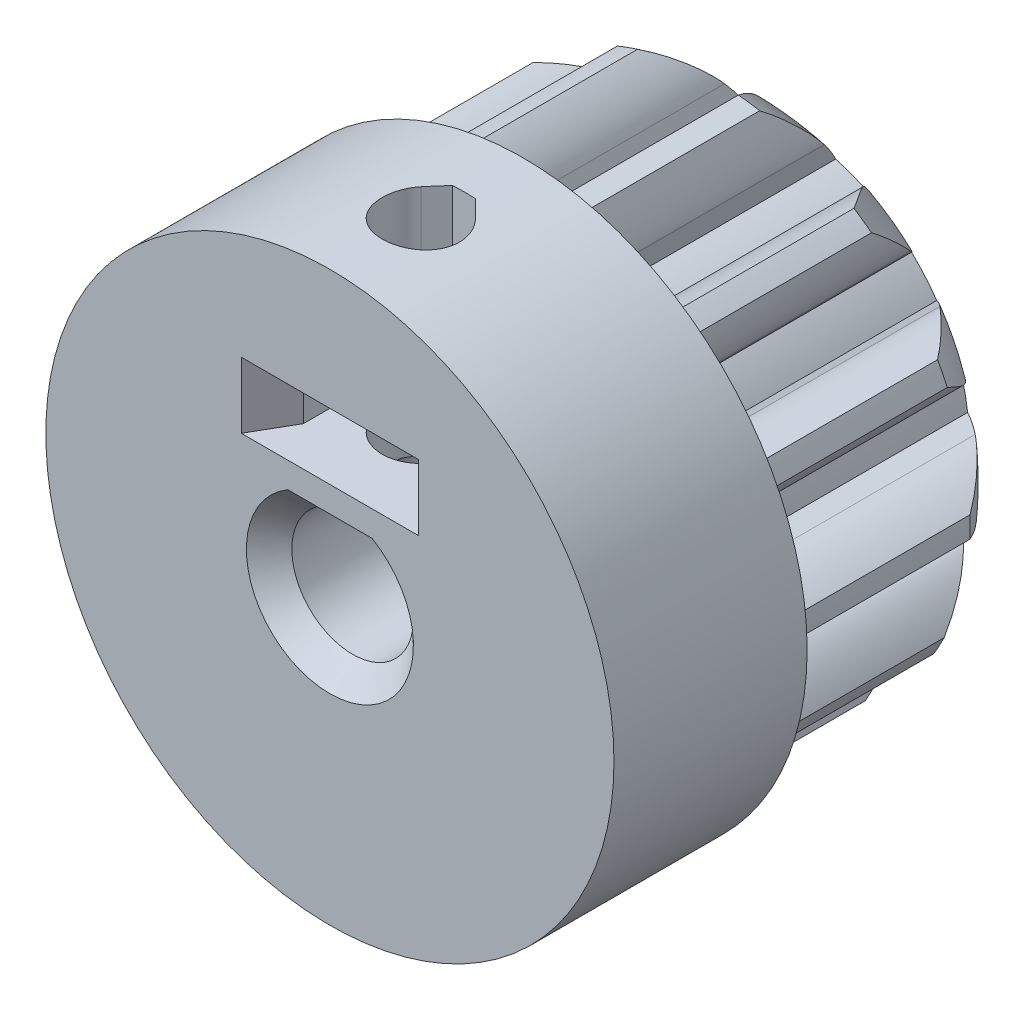
SolidWorks part; units mm, degrees
ref_plane "Alzado" through (0, 0, 0) normal (0, 0, 1) x (1, 0, 0)
ref_plane "Planta" through (0, 0, 0) normal (0, 1, 0) x (1, 0, 0)
ref_plane "Vista lateral" through (0, 0, 0) normal (1, 0, 0) x (0, 0, -1)
sketch "Croquis1" plane through (0, 0, 0) normal (0, 0, 1) x (1, 0, 0)
  circle A0 centre (0, 0) radius 12.5
  circle A1 centre (0, 0) radius 2.675
  dimension "D1" = 25
  dimension "D2" = 5.35
extrude "Saliente-Extruir1" add sketch "Croquis1" along normal blind 8.5
sketch "Croquis4" plane through (0, 0, 0) normal (0, 0, 1) x (1, 0, 0)
  line L27 (-1.6877, 7.8302) -> (-1.9305, 8.9563)
  line L29 (-4.2578, 8.1126) -> (-3.7224, 7.0925)
  line L41 (0, 9.162) -> (0, 8.01)
  line L55 (-5.1333, 6.149) -> (-5.8715, 7.0333)
  line L57 (-7.5402, 5.2046) -> (-6.5921, 4.5502)
  line L59 (-7.4028, 3.0591) -> (-8.4675, 3.499)
  line L61 (-9.0952, 1.1044) -> (-7.9516, 0.9655)
  line L63 (-7.9765, -0.7316) -> (-9.1237, -0.8368)
  line L65 (-8.5666, -3.2489) -> (-7.4895, -2.8404)
  line L67 (-6.7229, -4.3547) -> (-7.6898, -4.981)
  line L69 (-6.0755, -6.8579) -> (-5.3116, -5.9956)
  line L71 (-3.9291, -6.9801) -> (-4.4942, -7.984)
  line L73 (-2.1926, -8.8958) -> (-1.9169, -7.7772)
  line L75 (-0.2352, -8.0065) -> (-0.269, -9.1581)
  line L77 (2.1926, -8.8958) -> (1.9169, -7.7772)
  line L79 (3.5126, -7.1987) -> (4.0177, -8.2341)
  line L81 (6.0755, -6.8579) -> (5.3116, -5.9956)
  line L83 (6.4557, -4.7418) -> (7.3841, -5.4238)
  line L85 (8.5666, -3.2489) -> (7.4895, -2.8404)
  line L87 (7.9198, -1.1986) -> (9.0589, -1.3709)
  line L89 (9.0952, 1.1044) -> (7.9516, 0.9655)
  line L91 (7.5697, 2.6192) -> (8.6583, 2.9959)
  line L93 (7.5402, 5.2046) -> (6.5921, 4.5502)
  line L95 (5.4854, 5.837) -> (6.2743, 6.6765)
  line L97 (4.2578, 8.1126) -> (3.7224, 7.0925)
  line L99 (2.1445, 7.7176) -> (2.4529, 8.8276)
  circle A1 centre (0, 0) radius 9.75
  arc A4 (0, 8.01) -> (-1.6877, 7.8302) centre (0, 0) ccw
  arc A18 (-3.7224, 7.0925) -> (-5.1333, 6.149) centre (0, 0) ccw
  arc A20 (-6.5921, 4.5502) -> (-7.4028, 3.0591) centre (0, 0) ccw
  arc A22 (-7.9516, 0.9655) -> (-7.9765, -0.7316) centre (0, 0) ccw
  arc A24 (-7.4895, -2.8404) -> (-6.7229, -4.3547) centre (0, 0) ccw
  arc A26 (-5.3116, -5.9956) -> (-3.9291, -6.9801) centre (0, 0) ccw
  arc A28 (-1.9169, -7.7772) -> (-0.2352, -8.0065) centre (0, 0) ccw
  arc A30 (1.9169, -7.7772) -> (3.5126, -7.1987) centre (0, 0) ccw
  arc A32 (5.3116, -5.9956) -> (6.4557, -4.7418) centre (0, 0) ccw
  arc A34 (7.4895, -2.8404) -> (7.9198, -1.1986) centre (0, 0) ccw
  arc A36 (7.9516, 0.9655) -> (7.5697, 2.6192) centre (0, 0) ccw
  arc A38 (6.5921, 4.5502) -> (5.4854, 5.837) centre (0, 0) ccw
  arc A40 (3.7224, 7.0925) -> (2.1445, 7.7176) centre (0, 0) ccw
  spline S27 degree 3 poles (-1.9305, 8.9563) (-1.9308, 8.9581) (-1.9322, 8.9655) (-1.9374, 8.9814) (-1.9453, 9.0082) (-1.9584, 9.045) (-1.9766, 9.0919) (-2.0008, 9.1483) (-2.0318, 9.2139) (-2.0701, 9.2884) (-2.1164, 9.3712) (-2.1714, 9.4619) (-2.2356, 9.56) (-2.3096, 9.6649) (-2.394, 9.7761) (-2.4893, 9.8929) (-2.5959, 10.0147) (-2.7144, 10.1409) (-2.8451, 10.2707) (-2.9884, 10.4035) (-3.1448, 10.5385) (-3.3144, 10.6749) (-3.4977, 10.8121) (-3.6948, 10.9491) (-3.8803, 11.0688) (-4.0007, 11.1416) (-4.0498, 11.1706) knots 0.800768 0.800768 0.800768 0.800768 0.801125 0.802193 0.803973 0.806465 0.809669 0.813585 0.818213 0.823553 0.829605 0.836369 0.843845 0.852033 0.860933 0.870545 0.880869 0.891904 0.903652 0.916112 0.929284 0.943168 0.957764 0.973072 0.989092 1 1 1 1
  spline S29 degree 3 poles (-4.0498, 11.1706) (-4.069, 11.1169) (-4.1148, 10.9838) (-4.1805, 10.773) (-4.244, 10.5415) (-4.2968, 10.3188) (-4.3396, 10.1053) (-4.3731, 9.9015) (-4.398, 9.7077) (-4.4151, 9.5243) (-4.4252, 9.3515) (-4.429, 9.1896) (-4.4273, 9.0389) (-4.4208, 8.8995) (-4.4104, 8.7715) (-4.3969, 8.6551) (-4.3809, 8.5502) (-4.3634, 8.4569) (-4.3451, 8.3752) (-4.3268, 8.305) (-4.3093, 8.2461) (-4.2932, 8.1985) (-4.2796, 8.1619) (-4.2686, 8.1363) (-4.2623, 8.1207) (-4.2587, 8.1142) (-4.2578, 8.1126) knots 0.800768 0.800768 0.800768 0.800768 0.811676 0.827696 0.843004 0.8576 0.871484 0.884656 0.897116 0.908864 0.9199 0.930224 0.939836 0.948736 0.956924 0.964399 0.971163 0.977215 0.982555 0.987183 0.991099 0.994303 0.996795 0.998575 0.999644 1 1 1 1
  spline S31 degree 3 poles (1.6053, 11.7731) (1.5634, 11.7345) (1.461, 11.6379) (1.3048, 11.4818) (1.141, 11.3063) (0.9908, 11.1336) (0.8537, 10.9645) (0.7293, 10.7996) (0.6171, 10.6396) (0.5167, 10.4851) (0.4275, 10.3368) (0.3489, 10.1953) (0.2804, 10.061) (0.2213, 9.9346) (0.1711, 9.8164) (0.129, 9.707) (0.0944, 9.6068) (0.0665, 9.516) (0.0447, 9.4352) (0.0283, 9.3645) (0.0165, 9.3042) (0.0086, 9.2546) (0.0036, 9.2158) (0.0015, 9.188) (-0.0002, 9.1713) (0, 9.1639) (0, 9.162) knots 0.800768 0.800768 0.800768 0.800768 0.811676 0.827696 0.843004 0.8576 0.871484 0.884656 0.897116 0.908864 0.9199 0.930224 0.939836 0.948736 0.956924 0.964399 0.971163 0.977215 0.982555 0.987183 0.991099 0.994303 0.996795 0.998575 0.999644 1 1 1 1
  spline S45 degree 3 poles (-5.8715, 7.0333) (-5.8727, 7.0348) (-5.8774, 7.0406) (-5.8893, 7.0523) (-5.9088, 7.0723) (-5.9375, 7.0989) (-5.9753, 7.1319) (-6.0231, 7.1706) (-6.081, 7.2143) (-6.1495, 7.2624) (-6.229, 7.3142) (-6.3198, 7.369) (-6.4223, 7.426) (-6.5366, 7.4845) (-6.663, 7.5437) (-6.8016, 7.6029) (-6.9526, 7.6612) (-7.1162, 7.7179) (-7.2922, 7.7721) (-7.4809, 7.823) (-7.682, 7.8699) (-7.8957, 7.9119) (-8.1217, 7.9482) (-8.3599, 7.9779) (-8.5798, 7.9976) (-8.7202, 8.0062) (-8.7772, 8.009) knots 0.800768 0.800768 0.800768 0.800768 0.801125 0.802193 0.803973 0.806465 0.809669 0.813585 0.818213 0.823553 0.829605 0.836369 0.843845 0.852033 0.860933 0.870545 0.880869 0.891904 0.903652 0.916112 0.929284 0.943168 0.957764 0.973072 0.989092 1 1 1 1
  spline S47 degree 3 poles (-8.7772, 8.009) (-8.7692, 7.9525) (-8.7478, 7.8134) (-8.7081, 7.5963) (-8.6567, 7.3618) (-8.6, 7.14) (-8.5387, 6.9311) (-8.4736, 6.7351) (-8.4056, 6.5519) (-8.3356, 6.3815) (-8.2642, 6.2238) (-8.1923, 6.0788) (-8.1208, 5.9461) (-8.0503, 5.8257) (-7.9816, 5.7172) (-7.9154, 5.6204) (-7.8526, 5.5349) (-7.7937, 5.4605) (-7.7396, 5.3966) (-7.6907, 5.3429) (-7.6478, 5.299) (-7.6115, 5.2643) (-7.5824, 5.2381) (-7.5608, 5.2206) (-7.548, 5.2097) (-7.5417, 5.2056) (-7.5402, 5.2046) knots 0.800768 0.800768 0.800768 0.800768 0.811676 0.827696 0.843004 0.8576 0.871484 0.884656 0.897116 0.908864 0.9199 0.930224 0.939836 0.948736 0.956924 0.964399 0.971163 0.977215 0.982555 0.987183 0.991099 0.994303 0.996795 0.998575 0.999644 1 1 1 1
  spline S49 degree 3 poles (-8.4675, 3.499) (-8.4692, 3.4998) (-8.4761, 3.5028) (-8.4921, 3.5076) (-8.5186, 3.5163) (-8.5564, 3.5264) (-8.6053, 3.5381) (-8.6655, 3.5502) (-8.7371, 3.562) (-8.8201, 3.5728) (-8.9146, 3.5817) (-9.0205, 3.588) (-9.1377, 3.5908) (-9.2661, 3.5895) (-9.4055, 3.5832) (-9.5558, 3.5712) (-9.7166, 3.5526) (-9.8877, 3.5268) (-10.0688, 3.493) (-10.2595, 3.4504) (-10.4594, 3.3984) (-10.6681, 3.3363) (-10.8851, 3.2634) (-11.1098, 3.1791) (-11.3137, 3.0943) (-11.4421, 3.0366) (-11.4938, 3.0126) knots 0.800768 0.800768 0.800768 0.800768 0.801125 0.802193 0.803973 0.806465 0.809669 0.813585 0.818213 0.823553 0.829605 0.836369 0.843845 0.852033 0.860933 0.870545 0.880869 0.891904 0.903652 0.916112 0.929284 0.943168 0.957764 0.973072 0.989092 1 1 1 1
  spline S51 degree 3 poles (-11.4938, 3.0126) (-11.4605, 2.9664) (-11.3769, 2.8531) (-11.2408, 2.6793) (-11.0863, 2.4955) (-10.933, 2.3256) (-10.7817, 2.1691) (-10.6329, 2.0257) (-10.4876, 1.8951) (-10.3464, 1.7768) (-10.2099, 1.6704) (-10.0789, 1.5753) (-9.9539, 1.4911) (-9.8355, 1.4172) (-9.7242, 1.3531) (-9.6207, 1.2981) (-9.5253, 1.2516) (-9.4386, 1.2131) (-9.361, 1.1817) (-9.2928, 1.1569) (-9.2344, 1.1379) (-9.1861, 1.1241) (-9.1482, 1.1144) (-9.1208, 1.1089) (-9.1045, 1.1053) (-9.0971, 1.1045) (-9.0952, 1.1044) knots 0.800768 0.800768 0.800768 0.800768 0.811676 0.827696 0.843004 0.8576 0.871484 0.884656 0.897116 0.908864 0.9199 0.930224 0.939836 0.948736 0.956924 0.964399 0.971163 0.977215 0.982555 0.987183 0.991099 0.994303 0.996795 0.998575 0.999644 1 1 1 1
  spline S53 degree 3 poles (-9.1237, -0.8368) (-9.1256, -0.8369) (-9.133, -0.8375) (-9.1495, -0.8406) (-9.177, -0.8453) (-9.2151, -0.8539) (-9.2638, -0.8662) (-9.3227, -0.8835) (-9.3916, -0.9063) (-9.4702, -0.9354) (-9.558, -0.9714) (-9.6547, -1.015) (-9.7598, -1.067) (-9.8728, -1.1278) (-9.9934, -1.1982) (-10.1208, -1.2787) (-10.2546, -1.3698) (-10.3941, -1.4722) (-10.5388, -1.5863) (-10.6878, -1.7126) (-10.8407, -1.8516) (-10.9966, -2.0035) (-11.1548, -2.1689) (-11.3147, -2.3481) (-11.4558, -2.5178) (-11.5426, -2.6286) (-11.5773, -2.6739) knots 0.800768 0.800768 0.800768 0.800768 0.801125 0.802193 0.803973 0.806465 0.809669 0.813585 0.818213 0.823553 0.829605 0.836369 0.843845 0.852033 0.860933 0.870545 0.880869 0.891904 0.903652 0.916112 0.929284 0.943168 0.957764 0.973072 0.989092 1 1 1 1
  spline S55 degree 3 poles (-11.5773, -2.6739) (-11.5263, -2.6993) (-11.3997, -2.7608) (-11.1984, -2.8515) (-10.9762, -2.9424) (-10.7615, -3.0216) (-10.5547, -3.0899) (-10.3564, -3.1477) (-10.167, -3.1958) (-9.987, -3.2349) (-9.8167, -3.2658) (-9.6565, -3.289) (-9.5067, -3.3055) (-9.3675, -3.3159) (-9.2392, -3.321) (-9.122, -3.3216) (-9.0159, -3.3184) (-8.9212, -3.3122) (-8.8379, -3.3039) (-8.766, -3.2942) (-8.7054, -3.2839) (-8.6563, -3.2737) (-8.6182, -3.2646) (-8.5915, -3.2568) (-8.5753, -3.2524) (-8.5683, -3.2496) (-8.5666, -3.2489) knots 0.800768 0.800768 0.800768 0.800768 0.811676 0.827696 0.843004 0.8576 0.871484 0.884656 0.897116 0.908864 0.9199 0.930224 0.939836 0.948736 0.956924 0.964399 0.971163 0.977215 0.982555 0.987183 0.991099 0.994303 0.996795 0.998575 0.999644 1 1 1 1
  spline S57 degree 3 poles (-7.6898, -4.981) (-7.6913, -4.9819) (-7.6977, -4.9859) (-7.7108, -4.9963) (-7.733, -5.0132) (-7.7628, -5.0385) (-7.8001, -5.0721) (-7.8443, -5.1148) (-7.8947, -5.167) (-7.9507, -5.2293) (-8.0117, -5.302) (-8.0771, -5.3855) (-8.146, -5.4803) (-8.2179, -5.5868) (-8.2919, -5.7051) (-8.3673, -5.8356) (-8.4434, -5.9785) (-8.5193, -6.134) (-8.5944, -6.3022) (-8.6677, -6.4834) (-8.7385, -6.6774) (-8.8059, -6.8844) (-8.8692, -7.1044) (-8.9274, -7.3373) (-8.9735, -7.5532) (-8.9989, -7.6916) (-9.0086, -7.7478) knots 0.800768 0.800768 0.800768 0.800768 0.801125 0.802193 0.803973 0.806465 0.809669 0.813585 0.818213 0.823553 0.829605 0.836369 0.843845 0.852033 0.860933 0.870545 0.880869 0.891904 0.903652 0.916112 0.929284 0.943168 0.957764 0.973072 0.989092 1 1 1 1
  spline S59 degree 3 poles (-9.0086, -7.7478) (-8.9516, -7.7467) (-8.8109, -7.7423) (-8.5905, -7.729) (-8.3515, -7.7063) (-8.1246, -7.6766) (-7.9098, -7.6409) (-7.7073, -7.6) (-7.5173, -7.5546) (-7.3397, -7.5056) (-7.1746, -7.4537) (-7.0219, -7.3999) (-6.8816, -7.3448) (-6.7535, -7.2894) (-6.6376, -7.2342) (-6.5335, -7.1803) (-6.4411, -7.1282) (-6.3601, -7.0787) (-6.2902, -7.0326) (-6.231, -6.9906) (-6.1822, -6.9534) (-6.1434, -6.9215) (-6.1139, -6.8958) (-6.0939, -6.8764) (-6.0816, -6.865) (-6.0767, -6.8593) (-6.0755, -6.8579) knots 0.800768 0.800768 0.800768 0.800768 0.811676 0.827696 0.843004 0.8576 0.871484 0.884656 0.897116 0.908864 0.9199 0.930224 0.939836 0.948736 0.956924 0.964399 0.971163 0.977215 0.982555 0.987183 0.991099 0.994303 0.996795 0.998575 0.999644 1 1 1 1
  spline S61 degree 3 poles (-4.4942, -7.984) (-4.4951, -7.9856) (-4.4989, -7.992) (-4.5057, -8.0074) (-4.5174, -8.0327) (-4.5321, -8.0689) (-4.5495, -8.116) (-4.5688, -8.1744) (-4.5892, -8.244) (-4.6099, -8.3252) (-4.6301, -8.4179) (-4.6491, -8.5222) (-4.6661, -8.6382) (-4.6802, -8.7659) (-4.6908, -8.905) (-4.6969, -9.0556) (-4.6979, -9.2175) (-4.6929, -9.3905) (-4.6812, -9.5744) (-4.6619, -9.7688) (-4.6344, -9.9735) (-4.5979, -10.1882) (-4.5517, -10.4123) (-4.495, -10.6456) (-4.4355, -10.8582) (-4.3937, -10.9926) (-4.3761, -11.0468) knots 0.800768 0.800768 0.800768 0.800768 0.801125 0.802193 0.803973 0.806465 0.809669 0.813585 0.818213 0.823553 0.829605 0.836369 0.843845 0.852033 0.860933 0.870545 0.880869 0.891904 0.903652 0.916112 0.929284 0.943168 0.957764 0.973072 0.989092 1 1 1 1
  spline S63 degree 3 poles (-4.3761, -11.0468) (-4.3262, -11.0193) (-4.2037, -10.9501) (-4.0147, -10.8359) (-3.8136, -10.7047) (-3.6264, -10.573) (-3.4529, -10.4416) (-3.2926, -10.3112) (-3.1454, -10.1827) (-3.011, -10.0568) (-2.8889, -9.9342) (-2.7787, -9.8155) (-2.68, -9.7016) (-2.5924, -9.5929) (-2.5153, -9.4902) (-2.4483, -9.3941) (-2.3907, -9.305) (-2.3419, -9.2236) (-2.3014, -9.1503) (-2.2686, -9.0856) (-2.2427, -9.0299) (-2.2231, -8.9836) (-2.209, -8.9472) (-2.2002, -8.9207) (-2.1946, -8.9049) (-2.193, -8.8976) (-2.1926, -8.8958) knots 0.800768 0.800768 0.800768 0.800768 0.811676 0.827696 0.843004 0.8576 0.871484 0.884656 0.897116 0.908864 0.9199 0.930224 0.939836 0.948736 0.956924 0.964399 0.971163 0.977215 0.982555 0.987183 0.991099 0.994303 0.996795 0.998575 0.999644 1 1 1 1
  spline S65 degree 3 poles (-0.269, -9.1581) (-0.2691, -9.1599) (-0.2695, -9.1674) (-0.2683, -9.1841) (-0.267, -9.212) (-0.2631, -9.2509) (-0.2567, -9.3007) (-0.2466, -9.3613) (-0.2323, -9.4324) (-0.2129, -9.5139) (-0.1878, -9.6054) (-0.1561, -9.7066) (-0.1172, -9.8172) (-0.0705, -9.9368) (-0.0151, -10.0649) (0.0494, -10.2011) (0.1238, -10.3449) (0.2086, -10.4958) (0.3045, -10.6531) (0.4119, -10.8163) (0.5314, -10.9848) (0.6634, -11.1579) (0.8085, -11.3349) (0.9671, -11.5152) (1.1186, -11.6758) (1.2181, -11.7753) (1.2589, -11.8152) knots 0.800768 0.800768 0.800768 0.800768 0.801125 0.802193 0.803973 0.806465 0.809669 0.813585 0.818213 0.823553 0.829605 0.836369 0.843845 0.852033 0.860933 0.870545 0.880869 0.891904 0.903652 0.916112 0.929284 0.943168 0.957764 0.973072 0.989092 1 1 1 1
  spline S67 degree 3 poles (1.2589, -11.8152) (1.2903, -11.7676) (1.3666, -11.6493) (1.4809, -11.4604) (1.5979, -11.2508) (1.7025, -11.0472) (1.7951, -10.8502) (1.8764, -10.6603) (1.947, -10.4781) (2.0075, -10.3041) (2.0587, -10.1388) (2.1011, -9.9825) (2.1355, -9.8358) (2.1626, -9.6989) (2.1831, -9.5721) (2.1978, -9.4558) (2.2074, -9.3502) (2.2127, -9.2554) (2.2145, -9.1717) (2.2135, -9.0991) (2.2106, -9.0378) (2.2064, -8.9877) (2.202, -8.9489) (2.1974, -8.9214) (2.195, -8.9048) (2.1931, -8.8976) (2.1926, -8.8958) knots 0.800768 0.800768 0.800768 0.800768 0.811676 0.827696 0.843004 0.8576 0.871484 0.884656 0.897116 0.908864 0.9199 0.930224 0.939836 0.948736 0.956924 0.964399 0.971163 0.977215 0.982555 0.987183 0.991099 0.994303 0.996795 0.998575 0.999644 1 1 1 1
  spline S69 degree 3 poles (4.0177, -8.2341) (4.0185, -8.2358) (4.0217, -8.2425) (4.0305, -8.2568) (4.0446, -8.2809) (4.0661, -8.3135) (4.0949, -8.3546) (4.132, -8.4036) (4.1778, -8.4599) (4.2328, -8.5231) (4.2976, -8.5924) (4.3727, -8.6673) (4.4585, -8.7472) (4.5555, -8.8313) (4.664, -8.9191) (4.7845, -9.0097) (4.9172, -9.1025) (5.0624, -9.1966) (5.2203, -9.2914) (5.3913, -9.386) (5.5754, -9.4797) (5.7728, -9.5715) (5.9835, -9.6609) (6.2077, -9.7468) (6.4165, -9.8185) (6.5508, -9.8604) (6.6055, -9.8768) knots 0.800768 0.800768 0.800768 0.800768 0.801125 0.802193 0.803973 0.806465 0.809669 0.813585 0.818213 0.823553 0.829605 0.836369 0.843845 0.852033 0.860933 0.870545 0.880869 0.891904 0.903652 0.916112 0.929284 0.943168 0.957764 0.973072 0.989092 1 1 1 1
  spline S71 degree 3 poles (6.6055, -9.8768) (6.6112, -9.8201) (6.6238, -9.6799) (6.6372, -9.4595) (6.6434, -9.2195) (6.6414, -8.9907) (6.6318, -8.7731) (6.6156, -8.5672) (6.5934, -8.3731) (6.5662, -8.1909) (6.5346, -8.0207) (6.4995, -7.8627) (6.4618, -7.7167) (6.4222, -7.5829) (6.3814, -7.4612) (6.3404, -7.3513) (6.2998, -7.2533) (6.2605, -7.167) (6.2232, -7.092) (6.1886, -7.0282) (6.1575, -6.9752) (6.1305, -6.9329) (6.1085, -6.9005) (6.0917, -6.8783) (6.0819, -6.8647) (6.0768, -6.8592) (6.0755, -6.8579) knots 0.800768 0.800768 0.800768 0.800768 0.811676 0.827696 0.843004 0.8576 0.871484 0.884656 0.897116 0.908864 0.9199 0.930224 0.939836 0.948736 0.956924 0.964399 0.971163 0.977215 0.982555 0.987183 0.991099 0.994303 0.996795 0.998575 0.999644 1 1 1 1
  spline S73 degree 3 poles (7.3841, -5.4238) (7.3856, -5.4249) (7.3915, -5.4294) (7.4059, -5.438) (7.4296, -5.4527) (7.4638, -5.4716) (7.5085, -5.4947) (7.5641, -5.5208) (7.6308, -5.5494) (7.7088, -5.5797) (7.7984, -5.611) (7.8997, -5.6425) (8.0128, -5.6733) (8.1378, -5.7027) (8.2747, -5.73) (8.4235, -5.7542) (8.584, -5.7747) (8.7564, -5.7906) (8.9403, -5.8011) (9.1357, -5.8054) (9.3422, -5.8028) (9.5597, -5.7924) (9.7878, -5.7736) (10.0262, -5.7455) (10.2444, -5.712) (10.3829, -5.6866) (10.4388, -5.6757) knots 0.800768 0.800768 0.800768 0.800768 0.801125 0.802193 0.803973 0.806465 0.809669 0.813585 0.818213 0.823553 0.829605 0.836369 0.843845 0.852033 0.860933 0.870545 0.880869 0.891904 0.903652 0.916112 0.929284 0.943168 0.957764 0.973072 0.989092 1 1 1 1
  spline S75 degree 3 poles (10.4388, -5.6757) (10.4175, -5.6229) (10.3635, -5.4929) (10.273, -5.2915) (10.167, -5.0761) (10.0588, -4.8744) (9.9493, -4.6863) (9.8392, -4.5115) (9.7293, -4.3499) (9.6205, -4.2012) (9.5135, -4.0652) (9.409, -3.9416) (9.3078, -3.8299) (9.2105, -3.7298) (9.1179, -3.6409) (9.0305, -3.5628) (8.949, -3.4948) (8.874, -3.4366) (8.8062, -3.3876) (8.7459, -3.3472) (8.6937, -3.3147) (8.6501, -3.2898) (8.6157, -3.2713) (8.5904, -3.2595) (8.5754, -3.252) (8.5684, -3.2495) (8.5666, -3.2489) knots 0.800768 0.800768 0.800768 0.800768 0.811676 0.827696 0.843004 0.8576 0.871484 0.884656 0.897116 0.908864 0.9199 0.930224 0.939836 0.948736 0.956924 0.964399 0.971163 0.977215 0.982555 0.987183 0.991099 0.994303 0.996795 0.998575 0.999644 1 1 1 1
  spline S77 degree 3 poles (9.0589, -1.3709) (9.0607, -1.3713) (9.068, -1.3725) (9.0848, -1.3734) (9.1126, -1.3755) (9.1517, -1.3763) (9.2019, -1.3759) (9.2633, -1.3732) (9.3356, -1.3676) (9.4188, -1.3581) (9.5127, -1.3442) (9.617, -1.325) (9.7315, -1.2997) (9.8559, -1.2677) (9.9897, -1.2282) (10.1327, -1.1806) (10.2844, -1.124) (10.4444, -1.058) (10.6122, -0.9818) (10.7871, -0.8949) (10.9688, -0.7966) (11.1565, -0.6863) (11.3498, -0.5636) (11.5478, -0.4279) (11.7255, -0.2969) (11.8363, -0.2101) (11.8808, -0.1745) knots 0.800768 0.800768 0.800768 0.800768 0.801125 0.802193 0.803973 0.806465 0.809669 0.813585 0.818213 0.823553 0.829605 0.836369 0.843845 0.852033 0.860933 0.870545 0.880869 0.891904 0.903652 0.916112 0.929284 0.943168 0.957764 0.973072 0.989092 1 1 1 1
  spline S79 degree 3 poles (11.8808, -0.1745) (11.8373, -0.1375) (11.7291, -0.0475) (11.5554, 0.0887) (11.3614, 0.2301) (11.1719, 0.3585) (10.9875, 0.4742) (10.8088, 0.5778) (10.6364, 0.6698) (10.471, 0.7509) (10.313, 0.8216) (10.163, 0.8825) (10.0215, 0.9343) (9.8888, 0.9777) (9.7655, 1.0134) (9.6518, 1.042) (9.5481, 1.0643) (9.4547, 1.081) (9.3718, 1.0929) (9.2996, 1.1006) (9.2384, 1.1051) (9.1882, 1.107) (9.1491, 1.1073) (9.1212, 1.1061) (9.1044, 1.1057) (9.097, 1.1046) (9.0952, 1.1044) knots 0.800768 0.800768 0.800768 0.800768 0.811676 0.827696 0.843004 0.8576 0.871484 0.884656 0.897116 0.908864 0.9199 0.930224 0.939836 0.948736 0.956924 0.964399 0.971163 0.977215 0.982555 0.987183 0.991099 0.994303 0.996795 0.998575 0.999644 1 1 1 1
  spline S81 degree 3 poles (8.6583, 2.9959) (8.6601, 2.9965) (8.6672, 2.9988) (8.6824, 3.0058) (8.708, 3.0169) (8.743, 3.0344) (8.7873, 3.058) (8.8404, 3.0889) (8.9018, 3.1276) (8.9711, 3.1746) (9.0478, 3.2306) (9.1312, 3.2961) (9.2208, 3.3716) (9.3161, 3.4578) (9.4162, 3.5549) (9.5207, 3.6636) (9.6288, 3.7841) (9.7398, 3.9169) (9.8529, 4.0623) (9.9674, 4.2206) (10.0826, 4.3921) (10.1976, 4.577) (10.3116, 4.7754) (10.4239, 4.9876) (10.5203, 5.1862) (10.5781, 5.3145) (10.601, 5.3668) knots 0.800768 0.800768 0.800768 0.800768 0.801125 0.802193 0.803973 0.806465 0.809669 0.813585 0.818213 0.823553 0.829605 0.836369 0.843845 0.852033 0.860933 0.870545 0.880869 0.891904 0.903652 0.916112 0.929284 0.943168 0.957764 0.973072 0.989092 1 1 1 1
  spline S83 degree 3 poles (10.601, 5.3668) (10.5454, 5.3793) (10.4077, 5.4087) (10.1906, 5.4486) (9.9531, 5.4837) (9.7256, 5.5092) (9.5086, 5.526) (9.3022, 5.5347) (9.1068, 5.5361) (8.9226, 5.531) (8.7499, 5.5202) (8.5888, 5.5044) (8.4394, 5.4845) (8.3017, 5.4613) (8.176, 5.4356) (8.062, 5.4081) (7.9598, 5.3796) (7.8693, 5.351) (7.7904, 5.323) (7.7229, 5.2963) (7.6666, 5.2718) (7.6213, 5.2501) (7.5865, 5.2322) (7.5624, 5.2182) (7.5477, 5.2101) (7.5417, 5.2057) (7.5402, 5.2046) knots 0.800768 0.800768 0.800768 0.800768 0.811676 0.827696 0.843004 0.8576 0.871484 0.884656 0.897116 0.908864 0.9199 0.930224 0.939836 0.948736 0.956924 0.964399 0.971163 0.977215 0.982555 0.987183 0.991099 0.994303 0.996795 0.998575 0.999644 1 1 1 1
  spline S85 degree 3 poles (6.2743, 6.6765) (6.2756, 6.6778) (6.2808, 6.6832) (6.291, 6.6965) (6.3085, 6.7182) (6.3314, 6.7499) (6.3596, 6.7914) (6.3923, 6.8435) (6.4287, 6.9062) (6.4682, 6.98) (6.5101, 7.0652) (6.5535, 7.162) (6.5978, 7.2706) (6.6421, 7.3911) (6.6856, 7.5237) (6.7276, 7.6684) (6.7673, 7.8254) (6.8038, 7.9946) (6.8364, 8.1759) (6.8643, 8.3693) (6.8866, 8.5746) (6.9025, 8.7918) (6.9113, 9.0205) (6.9121, 9.2605) (6.9052, 9.4812) (6.8967, 9.6217) (6.8926, 9.6786) knots 0.800768 0.800768 0.800768 0.800768 0.801125 0.802193 0.803973 0.806465 0.809669 0.813585 0.818213 0.823553 0.829605 0.836369 0.843845 0.852033 0.860933 0.870545 0.880869 0.891904 0.903652 0.916112 0.929284 0.943168 0.957764 0.973072 0.989092 1 1 1 1
  spline S87 degree 3 poles (6.8926, 9.6786) (6.8376, 9.6638) (6.702, 9.6259) (6.4912, 9.5603) (6.2646, 9.481) (6.0514, 9.3979) (5.8514, 9.3119) (5.6646, 9.2236) (5.4909, 9.1341) (5.3302, 9.044) (5.1823, 8.9541) (5.047, 8.8653) (4.9239, 8.7783) (4.8128, 8.6938) (4.7134, 8.6125) (4.6253, 8.5352) (4.548, 8.4625) (4.4812, 8.3951) (4.4244, 8.3336) (4.377, 8.2787) (4.3385, 8.2308) (4.3085, 8.1905) (4.286, 8.1585) (4.2712, 8.1349) (4.2619, 8.1209) (4.2586, 8.1142) (4.2578, 8.1126) knots 0.800768 0.800768 0.800768 0.800768 0.811676 0.827696 0.843004 0.8576 0.871484 0.884656 0.897116 0.908864 0.9199 0.930224 0.939836 0.948736 0.956924 0.964399 0.971163 0.977215 0.982555 0.987183 0.991099 0.994303 0.996795 0.998575 0.999644 1 1 1 1
  spline S89 degree 3 poles (2.4529, 8.8276) (2.4534, 8.8293) (2.4556, 8.8365) (2.4584, 8.853) (2.4638, 8.8804) (2.4694, 8.9191) (2.475, 8.969) (2.4798, 9.0302) (2.4829, 9.1027) (2.4836, 9.1865) (2.481, 9.2813) (2.4745, 9.3872) (2.4632, 9.5039) (2.4464, 9.6312) (2.4234, 9.7688) (2.3933, 9.9165) (2.3555, 10.074) (2.3092, 10.2407) (2.2538, 10.4164) (2.1886, 10.6006) (2.1129, 10.7928) (2.0261, 10.9925) (1.9276, 11.1991) (1.8168, 11.412) (1.7081, 11.6042) (1.6353, 11.7246) (1.6053, 11.7731) knots 0.800768 0.800768 0.800768 0.800768 0.801125 0.802193 0.803973 0.806465 0.809669 0.813585 0.818213 0.823553 0.829605 0.836369 0.843845 0.852033 0.860933 0.870545 0.880869 0.891904 0.903652 0.916112 0.929284 0.943168 0.957764 0.973072 0.989092 1 1 1 1
  point P80 (-2.192, 9.5004)
  dimension "D1" = 19.5
extrude "Saliente-Extruir3" add sketch "Croquis4" against normal blind 8 contours S87 L97 A40 L99 S89 S31 L41 A4 L27 S27 S29 L29 A18 L55 S45 S47 L57 A20 L59 S49 S51 L61 A22 L63 S53 S55 L65 A24 L67 S57 S59 L69 A26 L71 S61 S63 L73 A28 L75 S65 S67 L77 A30 L79 S69 S71 L81 A32 L83 S73 S75 L85 A34 L87 S77 S79 L89 A36 L91 S81 S83 L93 A38 L95 S85
sketch "Croquis5" plane through (0, 0, -8) normal (0, 0, -1) x (-1, 0, 0)
  circle A0 centre (0, 0) radius 11.25
  circle A1 centre (0, 0) radius 13.8
  dimension "D1" = 22.5
extrude "Cortar-Extruir2" cut sketch "Croquis5" against normal up to surface (8 mm away) up to face at (0, 0, 0)
sketch "Croquis6" plane through (0, 0, 0) normal (0, 0, 1) x (1, 0, 0)
  circle A1 centre (0, 0) radius 2.675
  circle A2 centre (0, 0) radius 2.675
  dimension "D1" = 0
extrude "Cortar-Extruir3" cut sketch "Croquis6" against normal through all
ref_plane "Plano1" through (0, 4.3, 0) normal (0, 1, 0) x (1, 0, 0)
sketch "Croquis9" plane through (0, 0, 8.5) normal (0, 0, 1) x (1, 0, 0)
  line L0 (-1.5572, 2.175) -> (1.5572, 2.175)
  circle A0 centre (0, 0) radius 2.675 construction
  arc A1 (1.5572, 2.175) -> (-1.5572, 2.175) centre (0, 0) ccw
  dimension "D1" = 0.5
extrude "Saliente-Extruir4" add sketch "Croquis9" against normal through all
sketch "Croquis7" plane through (0, 4.3, 0) normal (0, 1, 0) x (1, 0, 0)
  line L0 (2.9, -8.5) -> (2.9, -6.1743)
  line L1 (-2.9, -8.5) -> (-2.9, -6.1743)
  line L2 (-12.5, -8.5) -> (12.5, -8.5) construction
  line L3 (-2.9, -8.5) -> (2.9, -8.5) construction
  line L4 (0, 0) -> (0, -8.5) construction
  line L5 (0, -4.5) -> (9.2818, -4.5) construction
  line L6 (-2.9, -2.8257) -> (-2.9, -6.1743)
  line L7 (-2.9, -6.1743) -> (0, -7.8486) construction
  line L8 (0, -7.8486) -> (2.9, -6.1743) construction
  line L9 (2.9, -6.1743) -> (2.9, -2.8257)
  line L10 (2.9, -2.8257) -> (0, -1.1514)
  line L11 (0, -1.1514) -> (-2.9, -2.8257)
  line L12 (2.9, -8.5) -> (-2.9, -8.5)
  line L13 (-2.9, -6.1743) -> (-2.9, -8.5)
  line L14 (2.9, -6.1743) -> (2.9, -8.5)
  circle A0 centre (0, -4.5) radius 2.9 construction
  dimension "D1" = 5.8
  dimension "D2" = 4
extrude "Cortar-Extruir4" cut sketch "Croquis7" along normal blind 2.9 contours L12 L0 L9 L10 L11 L6 L1 region at (0, 4.3, 5.2263)
sketch "Croquis8" plane through (0, 4.3, 0) normal (0, 1, 0) x (1, 0, 0)
  line L0 (-1.2021, -3.2979) -> (-0.5, -2.5958)
  line L1 (-0.5, -2.5958) -> (0.5, -2.5958)
  line L2 (0.5, -2.5958) -> (1.2021, -3.2979)
  line L5 (-2.9, -8.5) -> (2.9, -8.5)
  line L6 (2.9, -8.5) -> (2.9, -2.8257)
  line L7 (2.9, -2.8257) -> (0, -1.1514)
  line L8 (0, -1.1514) -> (-2.9, -2.8257)
  line L9 (-2.9, -2.8257) -> (-2.9, -8.5)
  line L10 (-2.9, -8.5) -> (2.9, -8.5) construction
  line L11 (2.9, -8.5) -> (2.9, -2.8257) construction
  line L12 (2.9, -2.8257) -> (0, -1.1514) construction
  line L13 (0, -1.1514) -> (-2.9, -2.8257) construction
  line L14 (-2.9, -2.8257) -> (-2.9, -8.5) construction
  circle A0 centre (0, -4.5) radius 2.9 construction
  arc A1 (-1.2021, -3.2979) -> (1.2021, -3.2979) centre (0, -4.5) ccw
  dimension "D2" = 3.4
  dimension "D3" = 1
  dimension "D4" = 90
  dimension "D1" = 0
extrude "Cortar-Extruir5" cut sketch "Croquis8" against normal up to next and the other way up to next
chamfer "Chaflán1" distance 1 angle 60 2 edges at (-2.9, 5.75, 8.5) (2.9, 5.75, 8.5) first distance on face at (0, 5.75, 8.5)
chamfer "Chaflán2" distance 1 angle 45 2 edges at (0, 2.175, 8.5) (0, -2.675, 8.5)
sketch "Croquis12" plane through (0, 0, 0) normal (0, 1, 0) x (1, 0, 0)
  line L0 (0, 13) -> (-3, 13)
  line L1 (0, 13) -> (0, 8)
  line L2 (0, 8) -> (-11.5, 8)
  line L3 (2.675, 8) -> (-2.675, 8) construction
  line L4 (0, 13) -> (0, 17.9892) construction
  line L5 (-12.5, -8.5) -> (12.5, -8.5) construction
  arc A0 (-3, 13) -> (-11.5, 8) centre (-3, 3.275) ccw
  dimension "D1" = 21.5
  dimension "D2" = 3
  dimension "D3" = 11.5
revolve "Revolución1" add sketch "Croquis12" angle 360 about L4
sketch "Croquis14" plane through (0, 0, -8) normal (0, 0, 1) x (1, 0, 0)
  line L0 (-1.5572, 2.175) -> (1.5572, 2.175) construction
  line L1 (-1.5572, 2.175) -> (1.5572, 2.175)
  line L26 (-7.4028, 3.0591) -> (-8.4675, 3.499)
  line L27 (-7.5402, 5.2046) -> (-6.5921, 4.5502)
  line L28 (-5.1333, 6.149) -> (-5.8715, 7.0333)
  line L29 (-4.2578, 8.1126) -> (-3.7224, 7.0925)
  line L30 (-1.6877, 7.8302) -> (-1.9305, 8.9563)
  line L31 (0, 9.162) -> (0, 8.01)
  line L32 (2.1445, 7.7176) -> (2.4529, 8.8276)
  line L33 (4.2578, 8.1126) -> (3.7224, 7.0925)
  line L34 (5.4854, 5.837) -> (6.2743, 6.6765)
  line L35 (7.5402, 5.2046) -> (6.5921, 4.5502)
  line L36 (7.5697, 2.6192) -> (8.6583, 2.9959)
  line L37 (9.0952, 1.1044) -> (7.9516, 0.9655)
  line L38 (7.9198, -1.1986) -> (9.0589, -1.3709)
  line L39 (8.5666, -3.2489) -> (7.4895, -2.8404)
  line L40 (6.4557, -4.7418) -> (7.3841, -5.4238)
  line L41 (6.0755, -6.8579) -> (5.3116, -5.9956)
  line L42 (3.5126, -7.1987) -> (4.0177, -8.2341)
  line L43 (2.1926, -8.8958) -> (1.9169, -7.7772)
  line L44 (-0.2352, -8.0065) -> (-0.269, -9.1581)
  line L45 (-2.1926, -8.8958) -> (-1.9169, -7.7772)
  line L46 (-3.9291, -6.9801) -> (-4.4942, -7.984)
  line L47 (-6.0755, -6.8579) -> (-5.3116, -5.9956)
  line L48 (-6.7229, -4.3547) -> (-7.6898, -4.981)
  line L49 (-8.5666, -3.2489) -> (-7.4895, -2.8404)
  line L50 (-7.9765, -0.7316) -> (-9.1237, -0.8368)
  line L51 (-9.0952, 1.1044) -> (-7.9516, 0.9655)
  line L52 (-7.4028, 3.0591) -> (-8.4675, 3.499)
  line L53 (-7.5402, 5.2046) -> (-6.5921, 4.5502)
  line L54 (-5.1333, 6.149) -> (-5.8715, 7.0333)
  line L55 (-4.2578, 8.1126) -> (-3.7224, 7.0925)
  line L56 (-1.6877, 7.8302) -> (-1.9305, 8.9563)
  line L57 (0, 9.162) -> (0, 8.01)
  line L58 (2.1445, 7.7176) -> (2.4529, 8.8276)
  line L59 (4.2578, 8.1126) -> (3.7224, 7.0925)
  line L60 (5.4854, 5.837) -> (6.2743, 6.6765)
  line L61 (7.5402, 5.2046) -> (6.5921, 4.5502)
  line L62 (7.5697, 2.6192) -> (8.6583, 2.9959)
  line L63 (9.0952, 1.1044) -> (7.9516, 0.9655)
  line L64 (7.9198, -1.1986) -> (9.0589, -1.3709)
  line L65 (8.5666, -3.2489) -> (7.4895, -2.8404)
  line L66 (6.4557, -4.7418) -> (7.3841, -5.4238)
  line L67 (6.0755, -6.8579) -> (5.3116, -5.9956)
  line L68 (3.5126, -7.1987) -> (4.0177, -8.2341)
  line L69 (2.1926, -8.8958) -> (1.9169, -7.7772)
  line L70 (-0.2352, -8.0065) -> (-0.269, -9.1581)
  line L71 (-2.1926, -8.8958) -> (-1.9169, -7.7772)
  line L72 (-3.9291, -6.9801) -> (-4.4942, -7.984)
  line L73 (-6.0755, -6.8579) -> (-5.3116, -5.9956)
  line L74 (-6.7229, -4.3547) -> (-7.6898, -4.981)
  line L75 (-8.5666, -3.2489) -> (-7.4895, -2.8404)
  line L76 (-7.9765, -0.7316) -> (-9.1237, -0.8368)
  line L77 (-9.0952, 1.1044) -> (-7.9516, 0.9655)
  arc A0 (-1.5572, 2.175) -> (1.5572, 2.175) centre (0, 0) ccw construction
  arc A1 (-1.5572, 2.175) -> (1.5572, 2.175) centre (0, 0) ccw
  arc A26 (-10.7528, 3.3075) -> (-10.9927, 2.3923) centre (0, 0) ccw
  arc A27 (-6.5921, 4.5502) -> (-7.4028, 3.0591) centre (0, 0) ccw
  arc A28 (-7.9841, 7.9257) -> (-8.6218, 7.2268) centre (0, 0) ccw
  arc A29 (-3.7224, 7.0925) -> (-5.1333, 6.149) centre (0, 0) ccw
  arc A30 (-3.3863, 10.7283) -> (-4.2758, 10.4058) centre (0, 0) ccw
  arc A31 (0, 8.01) -> (-1.6877, 7.8302) centre (0, 0) ccw
  arc A32 (1.9873, 11.0731) -> (1.0498, 11.2009) centre (0, 0) ccw
  arc A33 (3.7224, 7.0925) -> (2.1445, 7.7176) centre (0, 0) ccw
  arc A34 (6.9055, 8.8812) -> (6.1349, 9.43) centre (0, 0) ccw
  arc A35 (6.5921, 4.5502) -> (5.4854, 5.837) centre (0, 0) ccw
  arc A36 (10.2419, 4.6548) -> (9.8145, 5.4989) centre (0, 0) ccw
  arc A37 (7.9516, 0.9655) -> (7.5697, 2.6192) centre (0, 0) ccw
  arc A38 (11.2319, -0.638) -> (11.2458, 0.308) centre (0, 0) ccw
  arc A39 (7.4895, -2.8404) -> (7.9198, -1.1986) centre (0, 0) ccw
  arc A40 (9.6488, -5.7847) -> (10.1008, -4.9535) centre (0, 0) ccw
  arc A41 (5.3116, -5.9956) -> (6.4557, -4.7418) centre (0, 0) ccw
  arc A42 (5.8553, -9.6061) -> (6.6418, -9.0802) centre (0, 0) ccw
  arc A43 (1.9169, -7.7772) -> (3.5126, -7.1987) centre (0, 0) ccw
  arc A44 (0.7205, -11.2269) -> (1.6613, -11.1267) centre (0, 0) ccw
  arc A45 (-1.9169, -7.7772) -> (-0.2352, -8.0065) centre (0, 0) ccw
  arc A46 (-4.5795, -10.2757) -> (-3.6999, -10.6242) centre (0, 0) ccw
  arc A47 (-5.3116, -5.9956) -> (-3.9291, -6.9801) centre (0, 0) ccw
  arc A48 (-8.8303, -6.9705) -> (-8.2134, -7.6879) centre (0, 0) ccw
  arc A49 (-7.4895, -2.8404) -> (-6.7229, -4.3547) centre (0, 0) ccw
  arc A50 (-11.0582, -2.0685) -> (-10.8453, -2.9903) centre (0, 0) ccw
  arc A51 (-7.9516, 0.9655) -> (-7.9765, -0.7316) centre (0, 0) ccw
  arc A52 (-10.7528, 3.3075) -> (-10.9927, 2.3923) centre (0, 0) ccw
  arc A53 (-6.5921, 4.5502) -> (-7.4028, 3.0591) centre (0, 0) ccw
  arc A54 (-7.9841, 7.9257) -> (-8.6218, 7.2268) centre (0, 0) ccw
  arc A55 (-3.7224, 7.0925) -> (-5.1333, 6.149) centre (0, 0) ccw
  arc A56 (-3.3863, 10.7283) -> (-4.2758, 10.4058) centre (0, 0) ccw
  arc A57 (0, 8.01) -> (-1.6877, 7.8302) centre (0, 0) ccw
  arc A58 (1.9873, 11.0731) -> (1.0498, 11.2009) centre (0, 0) ccw
  arc A59 (3.7224, 7.0925) -> (2.1445, 7.7176) centre (0, 0) ccw
  arc A60 (6.9055, 8.8812) -> (6.1349, 9.43) centre (0, 0) ccw
  arc A61 (6.5921, 4.5502) -> (5.4854, 5.837) centre (0, 0) ccw
  arc A62 (10.2419, 4.6548) -> (9.8145, 5.4989) centre (0, 0) ccw
  arc A63 (7.9516, 0.9655) -> (7.5697, 2.6192) centre (0, 0) ccw
  arc A64 (11.2319, -0.638) -> (11.2458, 0.308) centre (0, 0) ccw
  arc A65 (7.4895, -2.8404) -> (7.9198, -1.1986) centre (0, 0) ccw
  arc A66 (9.6488, -5.7847) -> (10.1008, -4.9535) centre (0, 0) ccw
  arc A67 (5.3116, -5.9956) -> (6.4557, -4.7418) centre (0, 0) ccw
  arc A68 (5.8553, -9.6061) -> (6.6418, -9.0802) centre (0, 0) ccw
  arc A69 (1.9169, -7.7772) -> (3.5126, -7.1987) centre (0, 0) ccw
  arc A70 (0.7205, -11.2269) -> (1.6613, -11.1267) centre (0, 0) ccw
  arc A71 (-1.9169, -7.7772) -> (-0.2352, -8.0065) centre (0, 0) ccw
  arc A72 (-4.5795, -10.2757) -> (-3.6999, -10.6242) centre (0, 0) ccw
  arc A73 (-5.3116, -5.9956) -> (-3.9291, -6.9801) centre (0, 0) ccw
  arc A74 (-8.8303, -6.9705) -> (-8.2134, -7.6879) centre (0, 0) ccw
  arc A75 (-7.4895, -2.8404) -> (-6.7229, -4.3547) centre (0, 0) ccw
  arc A76 (-11.0582, -2.0685) -> (-10.8453, -2.9903) centre (0, 0) ccw
  arc A77 (-7.9516, 0.9655) -> (-7.9765, -0.7316) centre (0, 0) ccw
  spline S26 degree 3 poles (-435.114, -2966.9709) (75.3313, 156.2083) (-29.5037, 21.5216) (-10.7817, 2.1691) (-10.6329, 2.0257) (-10.4876, 1.8951) (-10.3464, 1.7768) (-10.2099, 1.6704) (-10.0789, 1.5753) (-9.9539, 1.4911) (-9.8355, 1.4172) (-9.7242, 1.3531) (-9.6207, 1.2981) (-9.5253, 1.2516) (-9.4386, 1.2131) (-9.361, 1.1817) (-9.2928, 1.1569) (-9.2344, 1.1379) (-9.1861, 1.1241) (-9.1482, 1.1144) (-9.1208, 1.1089) (-8.4186, 0.9522) (-6.5413, 8.8418) (-443.5898, -2964.9371) knots -4.266531 -4.266531 -4.266531 -4.266531 0.8576 0.871484 0.884656 0.897116 0.908864 0.9199 0.930224 0.939836 0.948736 0.956924 0.964399 0.971163 0.977215 0.982555 0.987183 0.991099 0.994303 0.996795 0.998575 0.999644 1.134193 1.134193 1.134193 1.134193 only from (-10.9927, 2.3923) to (-9.0952, 1.1044)
  spline S27 degree 3 poles (1067.6332, 2800.8573) (-10.0371, -4.4955) (-7.8033, 3.2998) (-8.4921, 3.5076) (-8.5186, 3.5163) (-8.5564, 3.5264) (-8.6053, 3.5381) (-8.6655, 3.5502) (-8.7371, 3.562) (-8.8201, 3.5728) (-8.9146, 3.5817) (-9.0205, 3.588) (-9.1377, 3.5908) (-9.2661, 3.5895) (-9.4055, 3.5832) (-9.5558, 3.5712) (-9.7166, 3.5526) (-9.8877, 3.5268) (-10.0688, 3.493) (-10.2595, 3.4504) (-10.4594, 3.3984) (-36.2672, -4.2823) (-10.9778, -173.0762) (1076.1966, 2798.9403) knots 0.666583 0.666583 0.666583 0.666583 0.801125 0.802193 0.803973 0.806465 0.809669 0.813585 0.818213 0.823553 0.829605 0.836369 0.843845 0.852033 0.860933 0.870545 0.880869 0.891904 0.903652 0.916112 0.929284 0.943168 6.067302 6.067302 6.067302 6.067302 only from (-8.4675, 3.499) to (-10.7528, 3.3075)
  spline S28 degree 3 poles (-1764.0944, -2424.9147) (139.2962, 103.3074) (-16.1226, 32.7675) (-8.5387, 6.9311) (-8.4736, 6.7351) (-8.4056, 6.5519) (-8.3356, 6.3815) (-8.2642, 6.2238) (-8.1923, 6.0788) (-8.1208, 5.9461) (-8.0503, 5.8257) (-7.9816, 5.7172) (-7.9154, 5.6204) (-7.8526, 5.5349) (-7.7937, 5.4605) (-7.7396, 5.3966) (-7.6907, 5.3429) (-7.6478, 5.299) (-7.6115, 5.2643) (-7.5824, 5.2381) (-7.5608, 5.2206) (-7.0118, 4.7555) (-1.6831, 10.8689) (-1770.6542, -2419.175) knots -4.266531 -4.266531 -4.266531 -4.266531 0.8576 0.871484 0.884656 0.897116 0.908864 0.9199 0.930224 0.939836 0.948736 0.956924 0.964399 0.971163 0.977215 0.982555 0.987183 0.991099 0.994303 0.996795 0.998575 0.999644 1.134193 1.134193 1.134193 1.134193 only from (-8.6218, 7.2268) to (-7.5402, 5.2046)
  spline S29 degree 3 poles (2246.9655, 1983.8821) (-10.9766, 0.684) (-5.376, 6.5482) (-5.8893, 7.0523) (-5.9088, 7.0723) (-5.9375, 7.0989) (-5.9753, 7.1319) (-6.0231, 7.1706) (-6.081, 7.2143) (-6.1495, 7.2624) (-6.229, 7.3142) (-6.3198, 7.369) (-6.4223, 7.426) (-6.5366, 7.4845) (-6.663, 7.5437) (-6.8016, 7.6029) (-6.9526, 7.6612) (-7.1162, 7.7179) (-7.2922, 7.7721) (-7.4809, 7.823) (-7.682, 7.8699) (-34.1031, 13.0624) (-90.1529, -148.1497) (2253.6572, 1978.205) knots 0.666583 0.666583 0.666583 0.666583 0.801125 0.802193 0.803973 0.806465 0.809669 0.813585 0.818213 0.823553 0.829605 0.836369 0.843845 0.852033 0.860933 0.870545 0.880869 0.891904 0.903652 0.916112 0.929284 0.943168 6.067302 6.067302 6.067302 6.067302 only from (-5.8715, 7.0333) to (-7.9841, 7.9257)
  spline S30 degree 3 poles (-2688.9421, -1327.3398) (171.35, 26.74) (0.9519, 36.5067) (-4.3396, 10.1053) (-4.3731, 9.9015) (-4.398, 9.7077) (-4.4151, 9.5243) (-4.4252, 9.3515) (-4.429, 9.1896) (-4.4273, 9.0389) (-4.4208, 8.8995) (-4.4104, 8.7715) (-4.3969, 8.6551) (-4.3809, 8.5502) (-4.3634, 8.4569) (-4.3451, 8.3752) (-4.3268, 8.305) (-4.3093, 8.2461) (-4.2932, 8.1985) (-4.2796, 8.1619) (-4.2686, 8.1363) (-3.9987, 7.4693) (3.5607, 10.4061) (-2692.0831, -1319.209) knots -4.266531 -4.266531 -4.266531 -4.266531 0.8576 0.871484 0.884656 0.897116 0.908864 0.9199 0.930224 0.939836 0.948736 0.956924 0.964399 0.971163 0.977215 0.982555 0.987183 0.991099 0.994303 0.996795 0.998575 0.999644 1.134193 1.134193 1.134193 1.134193 only from (-4.2758, 10.4058) to (-4.2578, 8.1126)
  spline S31 degree 3 poles (2911.5451, 712.4234) (-9.4014, 5.7067) (-1.7171, 8.2965) (-1.9374, 8.9814) (-1.9453, 9.0082) (-1.9584, 9.045) (-1.9766, 9.0919) (-2.0008, 9.1483) (-2.0318, 9.2139) (-2.0701, 9.2884) (-2.1164, 9.3712) (-2.1714, 9.4619) (-2.2356, 9.56) (-2.3096, 9.6649) (-2.394, 9.7761) (-2.4893, 9.8929) (-2.5959, 10.0147) (-2.7144, 10.1409) (-2.8451, 10.2707) (-2.9884, 10.4035) (-3.1448, 10.5385) (-24.1264, 27.4147) (-148.6751, -89.2839) (2914.832, 704.2868) knots 0.666583 0.666583 0.666583 0.666583 0.801125 0.802193 0.803973 0.806465 0.809669 0.813585 0.818213 0.823553 0.829605 0.836369 0.843845 0.852033 0.860933 0.870545 0.880869 0.891904 0.903652 0.916112 0.929284 0.943168 6.067302 6.067302 6.067302 6.067302 only from (-1.9305, 8.9563) to (-3.3863, 10.7283)
  spline S32 degree 3 poles (-2997.7856, 74.3127) (164.1496, -55.9532) (17.8084, 31.8827) (0.8537, 10.9645) (0.7293, 10.7996) (0.6171, 10.6396) (0.5167, 10.4851) (0.4275, 10.3368) (0.3489, 10.1953) (0.2804, 10.061) (0.2213, 9.9346) (0.1711, 9.8164) (0.129, 9.707) (0.0944, 9.6068) (0.0665, 9.516) (0.0447, 9.4352) (0.0283, 9.3645) (0.0165, 9.3042) (0.0086, 9.2546) (0.0036, 9.2158) (0.0015, 9.188) (-0.0695, 8.472) (7.9888, 7.5594) (-2996.7883, 82.9718) knots -4.266531 -4.266531 -4.266531 -4.266531 0.8576 0.871484 0.884656 0.897116 0.908864 0.9199 0.930224 0.939836 0.948736 0.956924 0.964399 0.971163 0.977215 0.982555 0.987183 0.991099 0.994303 0.996795 0.998575 0.999644 1.134193 1.134193 1.134193 1.134193 only from (1.0498, 11.2009) to (0, 9.162)
  spline S33 degree 3 poles (2909.1248, -722.2429) (-5.6725, 9.4221) (2.3351, 8.1442) (2.4584, 8.853) (2.4638, 8.8804) (2.4694, 8.9191) (2.475, 8.969) (2.4798, 9.0302) (2.4829, 9.1027) (2.4836, 9.1865) (2.481, 9.2813) (2.4745, 9.3872) (2.4632, 9.5039) (2.4464, 9.6312) (2.4234, 9.7688) (2.3933, 9.9165) (2.3555, 10.074) (2.3092, 10.2407) (2.2538, 10.4164) (2.1886, 10.6006) (2.1129, 10.7928) (-8.6226, 35.4866) (-173.1376, -9.9642) (2908.254, -730.975) knots 0.666583 0.666583 0.666583 0.666583 0.801125 0.802193 0.803973 0.806465 0.809669 0.813585 0.818213 0.823553 0.829605 0.836369 0.843845 0.852033 0.860933 0.870545 0.880869 0.891904 0.903652 0.916112 0.929284 0.943168 6.067302 6.067302 6.067302 6.067302 only from (2.4529, 8.8276) to (1.9873, 11.0731)
  spline S34 degree 3 poles (-2619.8724, 1458.941) (119.3445, -125.8282) (30.5852, 19.9548) (5.8514, 9.3119) (5.6646, 9.2236) (5.4909, 9.1341) (5.3302, 9.044) (5.1823, 8.9541) (5.047, 8.8653) (4.9239, 8.7783) (4.8128, 8.6938) (4.7134, 8.6125) (4.6253, 8.5352) (4.548, 8.4625) (4.4812, 8.3951) (4.4244, 8.3336) (4.377, 8.2787) (4.3385, 8.2308) (4.3085, 8.1905) (4.286, 8.1585) (4.2712, 8.1349) (3.8756, 7.5339) (10.5868, 2.9809) (-2614.9653, 1466.1448) knots -4.266531 -4.266531 -4.266531 -4.266531 0.8576 0.871484 0.884656 0.897116 0.908864 0.9199 0.930224 0.939836 0.948736 0.956924 0.964399 0.971163 0.977215 0.982555 0.987183 0.991099 0.994303 0.996795 0.998575 0.999644 1.134193 1.134193 1.134193 1.134193 only from (6.1349, 9.43) to (4.2578, 8.1126)
  spline S35 degree 3 poles (2240.2591, -1991.4521) (-0.6441, 10.979) (5.8524, 6.1261) (6.291, 6.6965) (6.3085, 6.7182) (6.3314, 6.7499) (6.3596, 6.7914) (6.3923, 6.8435) (6.4287, 6.9062) (6.4682, 6.98) (6.5101, 7.0652) (6.5535, 7.162) (6.5978, 7.2706) (6.6421, 7.3911) (6.6856, 7.5237) (6.7276, 7.6684) (6.7673, 7.8254) (6.8038, 7.9946) (6.8364, 8.1759) (6.8643, 8.3693) (6.8866, 8.5746) (8.8565, 35.429) (-157.9363, 71.6381) (2235.43, -1998.7792) knots 0.666583 0.666583 0.666583 0.666583 0.801125 0.802193 0.803973 0.806465 0.809669 0.813585 0.818213 0.823553 0.829605 0.836369 0.843845 0.852033 0.860933 0.870545 0.880869 0.891904 0.903652 0.916112 0.929284 0.943168 6.067302 6.067302 6.067302 6.067302 only from (6.2743, 6.6765) to (6.9055, 8.8812)
  spline S36 degree 3 poles (-1641.7781, 2509.3436) (47.199, -166.8775) (36.3553, 3.4554) (9.5086, 5.526) (9.3022, 5.5347) (9.1068, 5.5361) (8.9226, 5.531) (8.7499, 5.5202) (8.5888, 5.5044) (8.4394, 5.4845) (8.3017, 5.4613) (8.176, 5.4356) (8.062, 5.4081) (7.9598, 5.3796) (7.8693, 5.351) (7.7904, 5.323) (7.7229, 5.2963) (7.6666, 5.2718) (7.6213, 5.2501) (7.5865, 5.2322) (7.5624, 5.2182) (6.9328, 4.8698) (10.7594, -2.2805) (-1634.0853, 2513.4418) knots -4.266531 -4.266531 -4.266531 -4.266531 0.8576 0.871484 0.884656 0.897116 0.908864 0.9199 0.930224 0.939836 0.948736 0.956924 0.964399 0.971163 0.977215 0.982555 0.987183 0.991099 0.994303 0.996795 0.998575 0.999644 1.134193 1.134193 1.134193 1.134193 only from (9.8145, 5.4989) to (7.5402, 5.2046)
  spline S37 degree 3 poles (1058.177, -2804.4435) (4.5319, 10.0207) (8.029, 2.7047) (8.6824, 3.0058) (8.708, 3.0169) (8.743, 3.0344) (8.7873, 3.058) (8.8404, 3.0889) (8.9018, 3.1276) (8.9711, 3.1746) (9.0478, 3.2306) (9.1312, 3.2961) (9.2208, 3.3716) (9.3161, 3.4578) (9.4162, 3.5549) (9.5207, 3.6636) (9.6288, 3.7841) (9.7398, 3.9169) (9.8529, 4.0623) (9.9674, 4.2206) (10.0826, 4.3921) (24.3067, 27.255) (-106.5537, 136.8291) (1050.4959, -2808.6872) knots 0.666583 0.666583 0.666583 0.666583 0.801125 0.802193 0.803973 0.806465 0.809669 0.813585 0.818213 0.823553 0.829605 0.836369 0.843845 0.852033 0.860933 0.870545 0.880869 0.891904 0.903652 0.916112 0.929284 0.943168 6.067302 6.067302 6.067302 6.067302 only from (8.6583, 2.9959) to (10.2419, 4.6548)
  spline S38 degree 3 poles (-287.5722, 2984.8857) (-35.7592, -169.6972) (33.7968, -13.8355) (10.9875, 0.4742) (10.8088, 0.5778) (10.6364, 0.6698) (10.471, 0.7509) (10.313, 0.8216) (10.163, 0.8825) (10.0215, 0.9343) (9.8888, 0.9777) (9.7655, 1.0134) (9.6518, 1.042) (9.5481, 1.0643) (9.4547, 1.081) (9.3718, 1.0929) (9.2996, 1.1006) (9.2384, 1.1051) (9.1882, 1.107) (9.1491, 1.1073) (9.1212, 1.1061) (8.4019, 1.0902) (8.4672, -7.0194) (-278.856, 2984.9394) knots -4.266531 -4.266531 -4.266531 -4.266531 0.8576 0.871484 0.884656 0.897116 0.908864 0.9199 0.930224 0.939836 0.948736 0.956924 0.964399 0.971163 0.977215 0.982555 0.987183 0.991099 0.994303 0.996795 0.998575 0.999644 1.134193 1.134193 1.134193 1.134193 only from (11.2458, 0.308) to (9.0952, 1.1044)
  spline S39 degree 3 poles (-366.3207, -2974.9708) (8.6696, 6.7669) (8.3663, -1.3364) (9.0848, -1.3734) (9.1126, -1.3755) (9.1517, -1.3763) (9.2019, -1.3759) (9.2633, -1.3732) (9.3356, -1.3676) (9.4188, -1.3581) (9.5127, -1.3442) (9.617, -1.325) (9.7315, -1.2997) (9.8559, -1.2677) (9.9897, -1.2282) (10.1327, -1.1806) (10.2844, -1.124) (10.4444, -1.058) (10.6122, -0.9818) (10.7871, -0.8949) (10.9688, -0.7966) (34.1885, 12.8372) (-30.761, 170.6741) (-375.0941, -2975.1588) knots 0.666583 0.666583 0.666583 0.666583 0.801125 0.802193 0.803973 0.806465 0.809669 0.813585 0.818213 0.823553 0.829605 0.836369 0.843845 0.852033 0.860933 0.870545 0.880869 0.891904 0.903652 0.916112 0.929284 0.943168 6.067302 6.067302 6.067302 6.067302 only from (9.0589, -1.3709) to (11.2319, -0.638)
  spline S40 degree 3 poles (1132.513, 2776.6265) (-110.5254, -133.6412) (23.4959, -27.9569) (9.9493, -4.6863) (9.8392, -4.5115) (9.7293, -4.3499) (9.6205, -4.2012) (9.5135, -4.0652) (9.409, -3.9416) (9.3078, -3.8299) (9.2105, -3.7298) (9.1179, -3.6409) (9.0305, -3.5628) (8.949, -3.4948) (8.874, -3.4366) (8.8062, -3.3876) (8.7459, -3.3472) (8.6937, -3.3147) (8.6501, -3.2898) (8.6157, -3.2713) (8.5904, -3.2595) (7.9461, -2.9392) (4.2353, -10.1503) (1140.2558, 2772.6235) knots -4.266531 -4.266531 -4.266531 -4.266531 0.8576 0.871484 0.884656 0.897116 0.908864 0.9199 0.930224 0.939836 0.948736 0.956924 0.964399 0.971163 0.977215 0.982555 0.987183 0.991099 0.994303 0.996795 0.998575 0.999644 1.134193 1.134193 1.134193 1.134193 only from (10.1008, -4.9535) to (8.5666, -3.2489)
  spline S41 degree 3 poles (-1706.8987, -2463.9681) (10.8213, 1.9628) (6.7869, -5.0713) (7.4059, -5.438) (7.4296, -5.4527) (7.4638, -5.4716) (7.5085, -5.4947) (7.5641, -5.5208) (7.6308, -5.5494) (7.7088, -5.5797) (7.7984, -5.611) (7.8997, -5.6425) (8.0128, -5.6733) (8.1378, -5.7027) (8.2747, -5.73) (8.4235, -5.7542) (8.584, -5.7747) (8.7564, -5.7906) (8.9403, -5.8011) (9.1357, -5.8054) (9.3422, -5.8028) (36.2382, -4.5214) (52.0787, 165.4198) (-1714.7546, -2460.0574) knots 0.666583 0.666583 0.666583 0.666583 0.801125 0.802193 0.803973 0.806465 0.809669 0.813585 0.818213 0.823553 0.829605 0.836369 0.843845 0.852033 0.860933 0.870545 0.880869 0.891904 0.903652 0.916112 0.929284 0.943168 6.067302 6.067302 6.067302 6.067302 only from (7.3841, -5.4238) to (9.6488, -5.7847)
  spline S42 degree 3 poles (2293.1531, 1932.2757) (-159.9716, -66.9697) (7.8124, -35.6737) (6.6318, -8.7731) (6.6156, -8.5672) (6.5934, -8.3731) (6.5662, -8.1909) (6.5346, -8.0207) (6.4995, -7.8627) (6.4618, -7.7167) (6.4222, -7.5829) (6.3814, -7.4612) (6.3404, -7.3513) (6.2998, -7.2533) (6.2605, -7.167) (6.2232, -7.092) (6.1886, -7.0282) (6.1575, -6.9752) (6.1305, -6.9329) (6.1085, -6.9005) (6.0917, -6.8783) (5.67, -6.2953) (-0.9669, -10.9558) (2298.1487, 1925.1329) knots -4.266531 -4.266531 -4.266531 -4.266531 0.8576 0.871484 0.884656 0.897116 0.908864 0.9199 0.930224 0.939836 0.948736 0.956924 0.964399 0.971163 0.977215 0.982555 0.987183 0.991099 0.994303 0.996795 0.998575 0.999644 1.134193 1.134193 1.134193 1.134193 only from (6.6418, -9.0802) to (6.0755, -6.8579)
  spline S43 degree 3 poles (-2656.4468, -1388.5) (10.4939, -3.291) (3.6527, -7.6445) (4.0305, -8.2568) (4.0446, -8.2809) (4.0661, -8.3135) (4.0949, -8.3546) (4.132, -8.4036) (4.1778, -8.4599) (4.2328, -8.5231) (4.2976, -8.5924) (4.3727, -8.6673) (4.4585, -8.7472) (4.5555, -8.8313) (4.664, -8.9191) (4.7845, -9.0097) (4.9172, -9.1025) (5.0624, -9.1966) (5.2203, -9.2914) (5.3913, -9.386) (5.5754, -9.4797) (29.9861, -20.8442) (122.9878, 122.2698) (-2661.5855, -1381.3865) knots 0.666583 0.666583 0.666583 0.666583 0.801125 0.802193 0.803973 0.806465 0.809669 0.813585 0.818213 0.823553 0.829605 0.836369 0.843845 0.852033 0.860933 0.870545 0.880869 0.891904 0.903652 0.916112 0.929284 0.943168 6.067302 6.067302 6.067302 6.067302 only from (4.0177, -8.2341) to (5.8553, -9.6061)
  spline S44 degree 3 poles (2928.4595, 645.2637) (-172.7702, 15.0437) (-9.6609, -35.2181) (1.7951, -10.8502) (1.8764, -10.6603) (1.947, -10.4781) (2.0075, -10.3041) (2.0587, -10.1388) (2.1011, -9.9825) (2.1355, -9.8358) (2.1626, -9.6989) (2.1831, -9.5721) (2.1978, -9.4558) (2.2074, -9.3502) (2.2127, -9.2554) (2.2145, -9.1717) (2.2135, -9.0991) (2.2106, -9.0378) (2.2064, -8.9877) (2.202, -8.9489) (2.1974, -8.9214) (2.095, -8.2092) (-5.9476, -9.2516) (2929.5635, 636.6176) knots -4.266531 -4.266531 -4.266531 -4.266531 0.8576 0.871484 0.884656 0.897116 0.908864 0.9199 0.930224 0.939836 0.948736 0.956924 0.964399 0.971163 0.977215 0.982555 0.987183 0.991099 0.994303 0.996795 0.998575 0.999644 1.134193 1.134193 1.134193 1.134193 only from (1.6613, -11.1267) to (2.1926, -8.8958)
  spline S45 degree 3 poles (-2997.435, 5.0567) (7.7625, -7.7908) (-0.3182, -8.4664) (-0.2683, -9.1841) (-0.267, -9.212) (-0.2631, -9.2509) (-0.2567, -9.3007) (-0.2466, -9.3613) (-0.2323, -9.4324) (-0.2129, -9.5139) (-0.1878, -9.6054) (-0.1561, -9.7066) (-0.1172, -9.8172) (-0.0705, -9.9368) (-0.0151, -10.0649) (0.0494, -10.2011) (0.1238, -10.3449) (0.2086, -10.4958) (0.3045, -10.6531) (0.4119, -10.8163) (0.5314, -10.9848) (16.8646, -32.3919) (165.7219, 51.1092) (-2998.6792, 13.7435) knots 0.666583 0.666583 0.666583 0.666583 0.801125 0.802193 0.803973 0.806465 0.809669 0.813585 0.818213 0.823553 0.829605 0.836369 0.843845 0.852033 0.860933 0.870545 0.880869 0.891904 0.903652 0.916112 0.929284 0.943168 6.067302 6.067302 6.067302 6.067302 only from (-0.269, -9.1581) to (0.7205, -11.2269)
  spline S46 degree 3 poles (2892.8912, -789.5704) (-145.9892, 93.6109) (-24.921, -26.6944) (-3.4529, -10.4416) (-3.2926, -10.3112) (-3.1454, -10.1827) (-3.011, -10.0568) (-2.8889, -9.9342) (-2.7787, -9.8155) (-2.68, -9.7016) (-2.5924, -9.5929) (-2.5153, -9.4902) (-2.4483, -9.3941) (-2.3907, -9.305) (-2.3419, -9.2236) (-2.3014, -9.1503) (-2.2686, -9.0856) (-2.2427, -9.0299) (-2.2231, -8.9836) (-2.209, -8.9472) (-2.2002, -8.9207) (-1.96, -8.2425) (-9.5658, -5.4279) (2889.8506, -797.7392) knots -4.266531 -4.266531 -4.266531 -4.266531 0.8576 0.871484 0.884656 0.897116 0.908864 0.9199 0.930224 0.939836 0.948736 0.956924 0.964399 0.971163 0.977215 0.982555 0.987183 0.991099 0.994303 0.996795 0.998575 0.999644 1.134193 1.134193 1.134193 1.134193 only from (-3.6999, -10.6242) to (-2.1926, -8.8958)
  spline S47 degree 3 poles (-2651.7469, 1397.455) (3.2528, -10.5058) (-4.2163, -7.3487) (-4.5057, -8.0074) (-4.5174, -8.0327) (-4.5321, -8.0689) (-4.5495, -8.116) (-4.5688, -8.1744) (-4.5892, -8.244) (-4.6099, -8.3252) (-4.6301, -8.4179) (-4.6491, -8.5222) (-4.6661, -8.6382) (-4.6802, -8.7659) (-4.6908, -8.905) (-4.6969, -9.0556) (-4.6979, -9.2175) (-4.6929, -9.3905) (-4.6812, -9.5744) (-4.6619, -9.7688) (-4.6344, -9.9735) (-0.1204, -36.5189) (170.4911, -31.7598) (-2648.8117, 1405.7249) knots 0.666583 0.666583 0.666583 0.666583 0.801125 0.802193 0.803973 0.806465 0.809669 0.813585 0.818213 0.823553 0.829605 0.836369 0.843845 0.852033 0.860933 0.870545 0.880869 0.891904 0.903652 0.916112 0.929284 0.943168 6.067302 6.067302 6.067302 6.067302 only from (-4.4942, -7.984) to (-4.5795, -10.2757)
  spline S48 degree 3 poles (2194.5963, -2043.5234) (-85.7639, 150.7329) (-34.4719, -12.0554) (-7.9098, -7.6409) (-7.7073, -7.6) (-7.5173, -7.5546) (-7.3397, -7.5056) (-7.1746, -7.4537) (-7.0219, -7.3999) (-6.8816, -7.3448) (-6.7535, -7.2894) (-6.6376, -7.2342) (-6.5335, -7.1803) (-6.4411, -7.1282) (-6.3601, -7.0787) (-6.2902, -7.0326) (-6.231, -6.9906) (-6.1822, -6.9534) (-6.1434, -6.9215) (-6.1139, -6.8958) (-6.0939, -6.8764) (-5.566, -6.3875) (-10.9925, -0.3607) (2188.1077, -2049.3435) knots -4.266531 -4.266531 -4.266531 -4.266531 0.8576 0.871484 0.884656 0.897116 0.908864 0.9199 0.930224 0.939836 0.948736 0.956924 0.964399 0.971163 0.977215 0.982555 0.987183 0.991099 0.994303 0.996795 0.998575 0.999644 1.134193 1.134193 1.134193 1.134193 only from (-8.2134, -7.6879) to (-6.0755, -6.8579)
  spline S49 degree 3 poles (-1698.5756, 2469.7132) (-2.0021, -10.8141) (-7.1484, -4.5475) (-7.7108, -4.9963) (-7.733, -5.0132) (-7.7628, -5.0385) (-7.8001, -5.0721) (-7.8443, -5.1148) (-7.8947, -5.167) (-7.9507, -5.2293) (-8.0117, -5.302) (-8.0771, -5.3855) (-8.146, -5.4803) (-8.2179, -5.5868) (-8.2919, -5.7051) (-8.3673, -5.8356) (-8.4434, -5.9785) (-8.5193, -6.134) (-8.5944, -6.3022) (-8.6677, -6.4834) (-8.7385, -6.6774) (-17.0778, -32.28) (136.2028, -107.3531) (-1692.1333, 2475.6718) knots 0.666583 0.666583 0.666583 0.666583 0.801125 0.802193 0.803973 0.806465 0.809669 0.813585 0.818213 0.823553 0.829605 0.836369 0.843845 0.852033 0.860933 0.870545 0.880869 0.891904 0.903652 0.916112 0.929284 0.943168 6.067302 6.067302 6.067302 6.067302 only from (-7.6898, -4.981) to (-8.8303, -6.9705)
  spline S50 degree 3 poles (993.5458, -2829.3298) (-5.8911, 173.3238) (-36.1258, 5.3454) (-10.5547, -3.0899) (-10.3564, -3.1477) (-10.167, -3.1958) (-9.987, -3.2349) (-9.8167, -3.2658) (-9.6565, -3.289) (-9.5067, -3.3055) (-9.3675, -3.3159) (-9.2392, -3.321) (-9.122, -3.3216) (-9.0159, -3.3184) (-8.9212, -3.3122) (-8.8379, -3.3039) (-8.766, -3.2942) (-8.7054, -3.2839) (-8.6563, -3.2737) (-8.6182, -3.2646) (-8.5915, -3.2568) (-7.8968, -3.0692) (-9.901, 4.7891) (985.0958, -2831.4679) knots -4.266531 -4.266531 -4.266531 -4.266531 0.8576 0.871484 0.884656 0.897116 0.908864 0.9199 0.930224 0.939836 0.948736 0.956924 0.964399 0.971163 0.977215 0.982555 0.987183 0.991099 0.994303 0.996795 0.998575 0.999644 1.134193 1.134193 1.134193 1.134193 only from (-10.8453, -2.9903) to (-8.5666, -3.2489)
  spline S51 degree 3 poles (-356.281, 2976.1898) (-6.7983, -8.645) (-8.443, -0.7046) (-9.1495, -0.8406) (-9.177, -0.8453) (-9.2151, -0.8539) (-9.2638, -0.8662) (-9.3227, -0.8835) (-9.3916, -0.9063) (-9.4702, -0.9354) (-9.558, -0.9714) (-9.6547, -1.015) (-9.7598, -1.067) (-9.8728, -1.1278) (-9.9934, -1.1982) (-10.1208, -1.2787) (-10.2546, -1.3698) (-10.3941, -1.4722) (-10.5388, -1.5863) (-10.6878, -1.7126) (-10.8407, -1.8516) (-30.1229, -20.646) (70.7121, -158.3531) (-347.8076, 2978.472) knots 0.666583 0.666583 0.666583 0.666583 0.801125 0.802193 0.803973 0.806465 0.809669 0.813585 0.818213 0.823553 0.829605 0.836369 0.843845 0.852033 0.860933 0.870545 0.880869 0.891904 0.903652 0.916112 0.929284 0.943168 6.067302 6.067302 6.067302 6.067302 only from (-9.1237, -0.8368) to (-11.0582, -2.0685)
  spline S52 degree 3 poles (-10.9927, 2.3923) (-10.9718, 2.3693) (-10.9016, 2.2931) (-10.7817, 2.1691) (-10.6329, 2.0257) (-10.4876, 1.8951) (-10.3464, 1.7768) (-10.2099, 1.6704) (-10.0789, 1.5753) (-9.9539, 1.4911) (-9.8355, 1.4172) (-9.7242, 1.3531) (-9.6207, 1.2981) (-9.5253, 1.2516) (-9.4386, 1.2131) (-9.361, 1.1817) (-9.2928, 1.1569) (-9.2344, 1.1379) (-9.1861, 1.1241) (-9.1482, 1.1144) (-9.1208, 1.1089) (-9.1045, 1.1053) (-9.0971, 1.1045) (-9.0952, 1.1044) knots 0.851656 0.851656 0.851656 0.851656 0.8576 0.871484 0.884656 0.897116 0.908864 0.9199 0.930224 0.939836 0.948736 0.956924 0.964399 0.971163 0.977215 0.982555 0.987183 0.991099 0.994303 0.996795 0.998575 0.999644 1 1 1 1
  spline S53 degree 3 poles (-8.4675, 3.499) (-8.4692, 3.4998) (-8.4761, 3.5028) (-8.4921, 3.5076) (-8.5186, 3.5163) (-8.5564, 3.5264) (-8.6053, 3.5381) (-8.6655, 3.5502) (-8.7371, 3.562) (-8.8201, 3.5728) (-8.9146, 3.5817) (-9.0205, 3.588) (-9.1377, 3.5908) (-9.2661, 3.5895) (-9.4055, 3.5832) (-9.5558, 3.5712) (-9.7166, 3.5526) (-9.8877, 3.5268) (-10.0688, 3.493) (-10.2595, 3.4504) (-10.4594, 3.3984) (-10.6248, 3.3492) (-10.7233, 3.3173) (-10.7528, 3.3075) knots 0.800768 0.800768 0.800768 0.800768 0.801125 0.802193 0.803973 0.806465 0.809669 0.813585 0.818213 0.823553 0.829605 0.836369 0.843845 0.852033 0.860933 0.870545 0.880869 0.891904 0.903652 0.916112 0.929284 0.943168 0.949112 0.949112 0.949112 0.949112
  spline S54 degree 3 poles (-8.6218, 7.2268) (-8.614, 7.1967) (-8.5872, 7.0966) (-8.5387, 6.9311) (-8.4736, 6.7351) (-8.4056, 6.5519) (-8.3356, 6.3815) (-8.2642, 6.2238) (-8.1923, 6.0788) (-8.1208, 5.9461) (-8.0503, 5.8257) (-7.9816, 5.7172) (-7.9154, 5.6204) (-7.8526, 5.5349) (-7.7937, 5.4605) (-7.7396, 5.3966) (-7.6907, 5.3429) (-7.6478, 5.299) (-7.6115, 5.2643) (-7.5824, 5.2381) (-7.5608, 5.2206) (-7.548, 5.2097) (-7.5417, 5.2056) (-7.5402, 5.2046) knots 0.851656 0.851656 0.851656 0.851656 0.8576 0.871484 0.884656 0.897116 0.908864 0.9199 0.930224 0.939836 0.948736 0.956924 0.964399 0.971163 0.977215 0.982555 0.987183 0.991099 0.994303 0.996795 0.998575 0.999644 1 1 1 1
  spline S55 degree 3 poles (-5.8715, 7.0333) (-5.8727, 7.0348) (-5.8774, 7.0406) (-5.8893, 7.0523) (-5.9088, 7.0723) (-5.9375, 7.0989) (-5.9753, 7.1319) (-6.0231, 7.1706) (-6.081, 7.2143) (-6.1495, 7.2624) (-6.229, 7.3142) (-6.3198, 7.369) (-6.4223, 7.426) (-6.5366, 7.4845) (-6.663, 7.5437) (-6.8016, 7.6029) (-6.9526, 7.6612) (-7.1162, 7.7179) (-7.2922, 7.7721) (-7.4809, 7.823) (-7.682, 7.8699) (-7.8513, 7.9032) (-7.9534, 7.9207) (-7.9841, 7.9257) knots 0.800768 0.800768 0.800768 0.800768 0.801125 0.802193 0.803973 0.806465 0.809669 0.813585 0.818213 0.823553 0.829605 0.836369 0.843845 0.852033 0.860933 0.870545 0.880869 0.891904 0.903652 0.916112 0.929284 0.943168 0.949112 0.949112 0.949112 0.949112
  spline S56 degree 3 poles (-4.2758, 10.4058) (-4.2828, 10.3755) (-4.3057, 10.2744) (-4.3396, 10.1053) (-4.3731, 9.9015) (-4.398, 9.7077) (-4.4151, 9.5243) (-4.4252, 9.3515) (-4.429, 9.1896) (-4.4273, 9.0389) (-4.4208, 8.8995) (-4.4104, 8.7715) (-4.3969, 8.6551) (-4.3809, 8.5502) (-4.3634, 8.4569) (-4.3451, 8.3752) (-4.3268, 8.305) (-4.3093, 8.2461) (-4.2932, 8.1985) (-4.2796, 8.1619) (-4.2686, 8.1363) (-4.2623, 8.1207) (-4.2587, 8.1142) (-4.2578, 8.1126) knots 0.851656 0.851656 0.851656 0.851656 0.8576 0.871484 0.884656 0.897116 0.908864 0.9199 0.930224 0.939836 0.948736 0.956924 0.964399 0.971163 0.977215 0.982555 0.987183 0.991099 0.994303 0.996795 0.998575 0.999644 1 1 1 1
  spline S57 degree 3 poles (-1.9305, 8.9563) (-1.9308, 8.9581) (-1.9322, 8.9655) (-1.9374, 8.9814) (-1.9453, 9.0082) (-1.9584, 9.045) (-1.9766, 9.0919) (-2.0008, 9.1483) (-2.0318, 9.2139) (-2.0701, 9.2884) (-2.1164, 9.3712) (-2.1714, 9.4619) (-2.2356, 9.56) (-2.3096, 9.6649) (-2.394, 9.7761) (-2.4893, 9.8929) (-2.5959, 10.0147) (-2.7144, 10.1409) (-2.8451, 10.2707) (-2.9884, 10.4035) (-3.1448, 10.5385) (-3.2792, 10.6466) (-3.3615, 10.7096) (-3.3863, 10.7283) knots 0.800768 0.800768 0.800768 0.800768 0.801125 0.802193 0.803973 0.806465 0.809669 0.813585 0.818213 0.823553 0.829605 0.836369 0.843845 0.852033 0.860933 0.870545 0.880869 0.891904 0.903652 0.916112 0.929284 0.943168 0.949112 0.949112 0.949112 0.949112
  spline S58 degree 3 poles (1.0498, 11.2009) (1.0295, 11.1774) (0.9623, 11.0985) (0.8537, 10.9645) (0.7293, 10.7996) (0.6171, 10.6396) (0.5167, 10.4851) (0.4275, 10.3368) (0.3489, 10.1953) (0.2804, 10.061) (0.2213, 9.9346) (0.1711, 9.8164) (0.129, 9.707) (0.0944, 9.6068) (0.0665, 9.516) (0.0447, 9.4352) (0.0283, 9.3645) (0.0165, 9.3042) (0.0086, 9.2546) (0.0036, 9.2158) (0.0015, 9.188) (-0.0002, 9.1713) (0, 9.1639) (0, 9.162) knots 0.851656 0.851656 0.851656 0.851656 0.8576 0.871484 0.884656 0.897116 0.908864 0.9199 0.930224 0.939836 0.948736 0.956924 0.964399 0.971163 0.977215 0.982555 0.987183 0.991099 0.994303 0.996795 0.998575 0.999644 1 1 1 1
  spline S59 degree 3 poles (2.4529, 8.8276) (2.4534, 8.8293) (2.4556, 8.8365) (2.4584, 8.853) (2.4638, 8.8804) (2.4694, 8.9191) (2.475, 8.969) (2.4798, 9.0302) (2.4829, 9.1027) (2.4836, 9.1865) (2.481, 9.2813) (2.4745, 9.3872) (2.4632, 9.5039) (2.4464, 9.6312) (2.4234, 9.7688) (2.3933, 9.9165) (2.3555, 10.074) (2.3092, 10.2407) (2.2538, 10.4164) (2.1886, 10.6006) (2.1129, 10.7928) (2.0441, 10.951) (2.0005, 11.045) (1.9873, 11.0731) knots 0.800768 0.800768 0.800768 0.800768 0.801125 0.802193 0.803973 0.806465 0.809669 0.813585 0.818213 0.823553 0.829605 0.836369 0.843845 0.852033 0.860933 0.870545 0.880869 0.891904 0.903652 0.916112 0.929284 0.943168 0.949112 0.949112 0.949112 0.949112
  spline S60 degree 3 poles (6.1349, 9.43) (6.106, 9.4187) (6.0098, 9.38) (5.8514, 9.3119) (5.6646, 9.2236) (5.4909, 9.1341) (5.3302, 9.044) (5.1823, 8.9541) (5.047, 8.8653) (4.9239, 8.7783) (4.8128, 8.6938) (4.7134, 8.6125) (4.6253, 8.5352) (4.548, 8.4625) (4.4812, 8.3951) (4.4244, 8.3336) (4.377, 8.2787) (4.3385, 8.2308) (4.3085, 8.1905) (4.286, 8.1585) (4.2712, 8.1349) (4.2619, 8.1209) (4.2586, 8.1142) (4.2578, 8.1126) knots 0.851656 0.851656 0.851656 0.851656 0.8576 0.871484 0.884656 0.897116 0.908864 0.9199 0.930224 0.939836 0.948736 0.956924 0.964399 0.971163 0.977215 0.982555 0.987183 0.991099 0.994303 0.996795 0.998575 0.999644 1 1 1 1
  spline S61 degree 3 poles (6.2743, 6.6765) (6.2756, 6.6778) (6.2808, 6.6832) (6.291, 6.6965) (6.3085, 6.7182) (6.3314, 6.7499) (6.3596, 6.7914) (6.3923, 6.8435) (6.4287, 6.9062) (6.4682, 6.98) (6.5101, 7.0652) (6.5535, 7.162) (6.5978, 7.2706) (6.6421, 7.3911) (6.6856, 7.5237) (6.7276, 7.6684) (6.7673, 7.8254) (6.8038, 7.9946) (6.8364, 8.1759) (6.8643, 8.3693) (6.8866, 8.5746) (6.8992, 8.7467) (6.9042, 8.8502) (6.9055, 8.8812) knots 0.800768 0.800768 0.800768 0.800768 0.801125 0.802193 0.803973 0.806465 0.809669 0.813585 0.818213 0.823553 0.829605 0.836369 0.843845 0.852033 0.860933 0.870545 0.880869 0.891904 0.903652 0.916112 0.929284 0.943168 0.949112 0.949112 0.949112 0.949112
  spline S62 degree 3 poles (9.8145, 5.4989) (9.7836, 5.5022) (9.6805, 5.5127) (9.5086, 5.526) (9.3022, 5.5347) (9.1068, 5.5361) (8.9226, 5.531) (8.7499, 5.5202) (8.5888, 5.5044) (8.4394, 5.4845) (8.3017, 5.4613) (8.176, 5.4356) (8.062, 5.4081) (7.9598, 5.3796) (7.8693, 5.351) (7.7904, 5.323) (7.7229, 5.2963) (7.6666, 5.2718) (7.6213, 5.2501) (7.5865, 5.2322) (7.5624, 5.2182) (7.5477, 5.2101) (7.5417, 5.2057) (7.5402, 5.2046) knots 0.851656 0.851656 0.851656 0.851656 0.8576 0.871484 0.884656 0.897116 0.908864 0.9199 0.930224 0.939836 0.948736 0.956924 0.964399 0.971163 0.977215 0.982555 0.987183 0.991099 0.994303 0.996795 0.998575 0.999644 1 1 1 1
  spline S63 degree 3 poles (8.6583, 2.9959) (8.6601, 2.9965) (8.6672, 2.9988) (8.6824, 3.0058) (8.708, 3.0169) (8.743, 3.0344) (8.7873, 3.058) (8.8404, 3.0889) (8.9018, 3.1276) (8.9711, 3.1746) (9.0478, 3.2306) (9.1312, 3.2961) (9.2208, 3.3716) (9.3161, 3.4578) (9.4162, 3.5549) (9.5207, 3.6636) (9.6288, 3.7841) (9.7398, 3.9169) (9.8529, 4.0623) (9.9674, 4.2206) (10.0826, 4.3921) (10.1737, 4.5386) (10.2263, 4.6279) (10.2419, 4.6548) knots 0.800768 0.800768 0.800768 0.800768 0.801125 0.802193 0.803973 0.806465 0.809669 0.813585 0.818213 0.823553 0.829605 0.836369 0.843845 0.852033 0.860933 0.870545 0.880869 0.891904 0.903652 0.916112 0.929284 0.943168 0.949112 0.949112 0.949112 0.949112
  spline S64 degree 3 poles (11.2458, 0.308) (11.22, 0.3253) (11.1336, 0.3825) (10.9875, 0.4742) (10.8088, 0.5778) (10.6364, 0.6698) (10.471, 0.7509) (10.313, 0.8216) (10.163, 0.8825) (10.0215, 0.9343) (9.8888, 0.9777) (9.7655, 1.0134) (9.6518, 1.042) (9.5481, 1.0643) (9.4547, 1.081) (9.3718, 1.0929) (9.2996, 1.1006) (9.2384, 1.1051) (9.1882, 1.107) (9.1491, 1.1073) (9.1212, 1.1061) (9.1044, 1.1057) (9.097, 1.1046) (9.0952, 1.1044) knots 0.851656 0.851656 0.851656 0.851656 0.8576 0.871484 0.884656 0.897116 0.908864 0.9199 0.930224 0.939836 0.948736 0.956924 0.964399 0.971163 0.977215 0.982555 0.987183 0.991099 0.994303 0.996795 0.998575 0.999644 1 1 1 1
  spline S65 degree 3 poles (9.0589, -1.3709) (9.0607, -1.3713) (9.068, -1.3725) (9.0848, -1.3734) (9.1126, -1.3755) (9.1517, -1.3763) (9.2019, -1.3759) (9.2633, -1.3732) (9.3356, -1.3676) (9.4188, -1.3581) (9.5127, -1.3442) (9.617, -1.325) (9.7315, -1.2997) (9.8559, -1.2677) (9.9897, -1.2282) (10.1327, -1.1806) (10.2844, -1.124) (10.4444, -1.058) (10.6122, -0.9818) (10.7871, -0.8949) (10.9688, -0.7966) (11.1175, -0.7092) (11.2056, -0.6546) (11.2319, -0.638) knots 0.800768 0.800768 0.800768 0.800768 0.801125 0.802193 0.803973 0.806465 0.809669 0.813585 0.818213 0.823553 0.829605 0.836369 0.843845 0.852033 0.860933 0.870545 0.880869 0.891904 0.903652 0.916112 0.929284 0.943168 0.949112 0.949112 0.949112 0.949112
  spline S66 degree 3 poles (10.1008, -4.9535) (10.086, -4.9262) (10.036, -4.8354) (9.9493, -4.6863) (9.8392, -4.5115) (9.7293, -4.3499) (9.6205, -4.2012) (9.5135, -4.0652) (9.409, -3.9416) (9.3078, -3.8299) (9.2105, -3.7298) (9.1179, -3.6409) (9.0305, -3.5628) (8.949, -3.4948) (8.874, -3.4366) (8.8062, -3.3876) (8.7459, -3.3472) (8.6937, -3.3147) (8.6501, -3.2898) (8.6157, -3.2713) (8.5904, -3.2595) (8.5754, -3.252) (8.5684, -3.2495) (8.5666, -3.2489) knots 0.851656 0.851656 0.851656 0.851656 0.8576 0.871484 0.884656 0.897116 0.908864 0.9199 0.930224 0.939836 0.948736 0.956924 0.964399 0.971163 0.977215 0.982555 0.987183 0.991099 0.994303 0.996795 0.998575 0.999644 1 1 1 1
  spline S67 degree 3 poles (7.3841, -5.4238) (7.3856, -5.4249) (7.3915, -5.4294) (7.4059, -5.438) (7.4296, -5.4527) (7.4638, -5.4716) (7.5085, -5.4947) (7.5641, -5.5208) (7.6308, -5.5494) (7.7088, -5.5797) (7.7984, -5.611) (7.8997, -5.6425) (8.0128, -5.6733) (8.1378, -5.7027) (8.2747, -5.73) (8.4235, -5.7542) (8.584, -5.7747) (8.7564, -5.7906) (8.9403, -5.8011) (9.1357, -5.8054) (9.3422, -5.8028) (9.5145, -5.7946) (9.6179, -5.7871) (9.6488, -5.7847) knots 0.800768 0.800768 0.800768 0.800768 0.801125 0.802193 0.803973 0.806465 0.809669 0.813585 0.818213 0.823553 0.829605 0.836369 0.843845 0.852033 0.860933 0.870545 0.880869 0.891904 0.903652 0.916112 0.929284 0.943168 0.949112 0.949112 0.949112 0.949112
  spline S68 degree 3 poles (6.6418, -9.0802) (6.6414, -9.0491) (6.6394, -8.9455) (6.6318, -8.7731) (6.6156, -8.5672) (6.5934, -8.3731) (6.5662, -8.1909) (6.5346, -8.0207) (6.4995, -7.8627) (6.4618, -7.7167) (6.4222, -7.5829) (6.3814, -7.4612) (6.3404, -7.3513) (6.2998, -7.2533) (6.2605, -7.167) (6.2232, -7.092) (6.1886, -7.0282) (6.1575, -6.9752) (6.1305, -6.9329) (6.1085, -6.9005) (6.0917, -6.8783) (6.0819, -6.8647) (6.0768, -6.8592) (6.0755, -6.8579) knots 0.851656 0.851656 0.851656 0.851656 0.8576 0.871484 0.884656 0.897116 0.908864 0.9199 0.930224 0.939836 0.948736 0.956924 0.964399 0.971163 0.977215 0.982555 0.987183 0.991099 0.994303 0.996795 0.998575 0.999644 1 1 1 1
  spline S69 degree 3 poles (4.0177, -8.2341) (4.0185, -8.2358) (4.0217, -8.2425) (4.0305, -8.2568) (4.0446, -8.2809) (4.0661, -8.3135) (4.0949, -8.3546) (4.132, -8.4036) (4.1778, -8.4599) (4.2328, -8.5231) (4.2976, -8.5924) (4.3727, -8.6673) (4.4585, -8.7472) (4.5555, -8.8313) (4.664, -8.9191) (4.7845, -9.0097) (4.9172, -9.1025) (5.0624, -9.1966) (5.2203, -9.2914) (5.3913, -9.386) (5.5754, -9.4797) (5.7318, -9.5525) (5.8268, -9.5939) (5.8553, -9.6061) knots 0.800768 0.800768 0.800768 0.800768 0.801125 0.802193 0.803973 0.806465 0.809669 0.813585 0.818213 0.823553 0.829605 0.836369 0.843845 0.852033 0.860933 0.870545 0.880869 0.891904 0.903652 0.916112 0.929284 0.943168 0.949112 0.949112 0.949112 0.949112
  spline S70 degree 3 poles (1.6613, -11.1267) (1.6753, -11.099) (1.7217, -11.0063) (1.7951, -10.8502) (1.8764, -10.6603) (1.947, -10.4781) (2.0075, -10.3041) (2.0587, -10.1388) (2.1011, -9.9825) (2.1355, -9.8358) (2.1626, -9.6989) (2.1831, -9.5721) (2.1978, -9.4558) (2.2074, -9.3502) (2.2127, -9.2554) (2.2145, -9.1717) (2.2135, -9.0991) (2.2106, -9.0378) (2.2064, -8.9877) (2.202, -8.9489) (2.1974, -8.9214) (2.195, -8.9048) (2.1931, -8.8976) (2.1926, -8.8958) knots 0.851656 0.851656 0.851656 0.851656 0.8576 0.871484 0.884656 0.897116 0.908864 0.9199 0.930224 0.939836 0.948736 0.956924 0.964399 0.971163 0.977215 0.982555 0.987183 0.991099 0.994303 0.996795 0.998575 0.999644 1 1 1 1
  spline S71 degree 3 poles (-0.269, -9.1581) (-0.2691, -9.1599) (-0.2695, -9.1674) (-0.2683, -9.1841) (-0.267, -9.212) (-0.2631, -9.2509) (-0.2567, -9.3007) (-0.2466, -9.3613) (-0.2323, -9.4324) (-0.2129, -9.5139) (-0.1878, -9.6054) (-0.1561, -9.7066) (-0.1172, -9.8172) (-0.0705, -9.9368) (-0.0151, -10.0649) (0.0494, -10.2011) (0.1238, -10.3449) (0.2086, -10.4958) (0.3045, -10.6531) (0.4119, -10.8163) (0.5314, -10.9848) (0.636, -11.122) (0.7008, -11.2028) (0.7205, -11.2269) knots 0.800768 0.800768 0.800768 0.800768 0.801125 0.802193 0.803973 0.806465 0.809669 0.813585 0.818213 0.823553 0.829605 0.836369 0.843845 0.852033 0.860933 0.870545 0.880869 0.891904 0.903652 0.916112 0.929284 0.943168 0.949112 0.949112 0.949112 0.949112
  spline S72 degree 3 poles (-3.6999, -10.6242) (-3.6745, -10.6062) (-3.5904, -10.5457) (-3.4529, -10.4416) (-3.2926, -10.3112) (-3.1454, -10.1827) (-3.011, -10.0568) (-2.8889, -9.9342) (-2.7787, -9.8155) (-2.68, -9.7016) (-2.5924, -9.5929) (-2.5153, -9.4902) (-2.4483, -9.3941) (-2.3907, -9.305) (-2.3419, -9.2236) (-2.3014, -9.1503) (-2.2686, -9.0856) (-2.2427, -9.0299) (-2.2231, -8.9836) (-2.209, -8.9472) (-2.2002, -8.9207) (-2.1946, -8.9049) (-2.193, -8.8976) (-2.1926, -8.8958) knots 0.851656 0.851656 0.851656 0.851656 0.8576 0.871484 0.884656 0.897116 0.908864 0.9199 0.930224 0.939836 0.948736 0.956924 0.964399 0.971163 0.977215 0.982555 0.987183 0.991099 0.994303 0.996795 0.998575 0.999644 1 1 1 1
  spline S73 degree 3 poles (-4.4942, -7.984) (-4.4951, -7.9856) (-4.4989, -7.992) (-4.5057, -8.0074) (-4.5174, -8.0327) (-4.5321, -8.0689) (-4.5495, -8.116) (-4.5688, -8.1744) (-4.5892, -8.244) (-4.6099, -8.3252) (-4.6301, -8.4179) (-4.6491, -8.5222) (-4.6661, -8.6382) (-4.6802, -8.7659) (-4.6908, -8.905) (-4.6969, -9.0556) (-4.6979, -9.2175) (-4.6929, -9.3905) (-4.6812, -9.5744) (-4.6619, -9.7688) (-4.6344, -9.9735) (-4.6055, -10.1436) (-4.5856, -10.2453) (-4.5795, -10.2757) knots 0.800768 0.800768 0.800768 0.800768 0.801125 0.802193 0.803973 0.806465 0.809669 0.813585 0.818213 0.823553 0.829605 0.836369 0.843845 0.852033 0.860933 0.870545 0.880869 0.891904 0.903652 0.916112 0.929284 0.943168 0.949112 0.949112 0.949112 0.949112
  spline S74 degree 3 poles (-8.2134, -7.6879) (-8.1826, -7.6837) (-8.08, -7.6692) (-7.9098, -7.6409) (-7.7073, -7.6) (-7.5173, -7.5546) (-7.3397, -7.5056) (-7.1746, -7.4537) (-7.0219, -7.3999) (-6.8816, -7.3448) (-6.7535, -7.2894) (-6.6376, -7.2342) (-6.5335, -7.1803) (-6.4411, -7.1282) (-6.3601, -7.0787) (-6.2902, -7.0326) (-6.231, -6.9906) (-6.1822, -6.9534) (-6.1434, -6.9215) (-6.1139, -6.8958) (-6.0939, -6.8764) (-6.0816, -6.865) (-6.0767, -6.8593) (-6.0755, -6.8579) knots 0.851656 0.851656 0.851656 0.851656 0.8576 0.871484 0.884656 0.897116 0.908864 0.9199 0.930224 0.939836 0.948736 0.956924 0.964399 0.971163 0.977215 0.982555 0.987183 0.991099 0.994303 0.996795 0.998575 0.999644 1 1 1 1
  spline S75 degree 3 poles (-7.6898, -4.981) (-7.6913, -4.9819) (-7.6977, -4.9859) (-7.7108, -4.9963) (-7.733, -5.0132) (-7.7628, -5.0385) (-7.8001, -5.0721) (-7.8443, -5.1148) (-7.8947, -5.167) (-7.9507, -5.2293) (-8.0117, -5.302) (-8.0771, -5.3855) (-8.146, -5.4803) (-8.2179, -5.5868) (-8.2919, -5.7051) (-8.3673, -5.8356) (-8.4434, -5.9785) (-8.5193, -6.134) (-8.5944, -6.3022) (-8.6677, -6.4834) (-8.7385, -6.6774) (-8.7919, -6.8414) (-8.8216, -6.9407) (-8.8303, -6.9705) knots 0.800768 0.800768 0.800768 0.800768 0.801125 0.802193 0.803973 0.806465 0.809669 0.813585 0.818213 0.823553 0.829605 0.836369 0.843845 0.852033 0.860933 0.870545 0.880869 0.891904 0.903652 0.916112 0.929284 0.943168 0.949112 0.949112 0.949112 0.949112
  spline S76 degree 3 poles (-10.8453, -2.9903) (-10.8161, -3.001) (-10.7185, -3.0358) (-10.5547, -3.0899) (-10.3564, -3.1477) (-10.167, -3.1958) (-9.987, -3.2349) (-9.8167, -3.2658) (-9.6565, -3.289) (-9.5067, -3.3055) (-9.3675, -3.3159) (-9.2392, -3.321) (-9.122, -3.3216) (-9.0159, -3.3184) (-8.9212, -3.3122) (-8.8379, -3.3039) (-8.766, -3.2942) (-8.7054, -3.2839) (-8.6563, -3.2737) (-8.6182, -3.2646) (-8.5915, -3.2568) (-8.5753, -3.2524) (-8.5683, -3.2496) (-8.5666, -3.2489) knots 0.851656 0.851656 0.851656 0.851656 0.8576 0.871484 0.884656 0.897116 0.908864 0.9199 0.930224 0.939836 0.948736 0.956924 0.964399 0.971163 0.977215 0.982555 0.987183 0.991099 0.994303 0.996795 0.998575 0.999644 1 1 1 1
  spline S77 degree 3 poles (-9.1237, -0.8368) (-9.1256, -0.8369) (-9.133, -0.8375) (-9.1495, -0.8406) (-9.177, -0.8453) (-9.2151, -0.8539) (-9.2638, -0.8662) (-9.3227, -0.8835) (-9.3916, -0.9063) (-9.4702, -0.9354) (-9.558, -0.9714) (-9.6547, -1.015) (-9.7598, -1.067) (-9.8728, -1.1278) (-9.9934, -1.1982) (-10.1208, -1.2787) (-10.2546, -1.3698) (-10.3941, -1.4722) (-10.5388, -1.5863) (-10.6878, -1.7126) (-10.8407, -1.8516) (-10.9642, -1.972) (-11.0367, -2.0461) (-11.0582, -2.0685) knots 0.800768 0.800768 0.800768 0.800768 0.801125 0.802193 0.803973 0.806465 0.809669 0.813585 0.818213 0.823553 0.829605 0.836369 0.843845 0.852033 0.860933 0.870545 0.880869 0.891904 0.903652 0.916112 0.929284 0.943168 0.949112 0.949112 0.949112 0.949112
  dimension "D1" = 0
extrude "Cortar-Extruir7" cut sketch "Croquis14" against normal through all flip side to cut
combine bodies "Combinar1" operation type add bodies to combine 112 117
